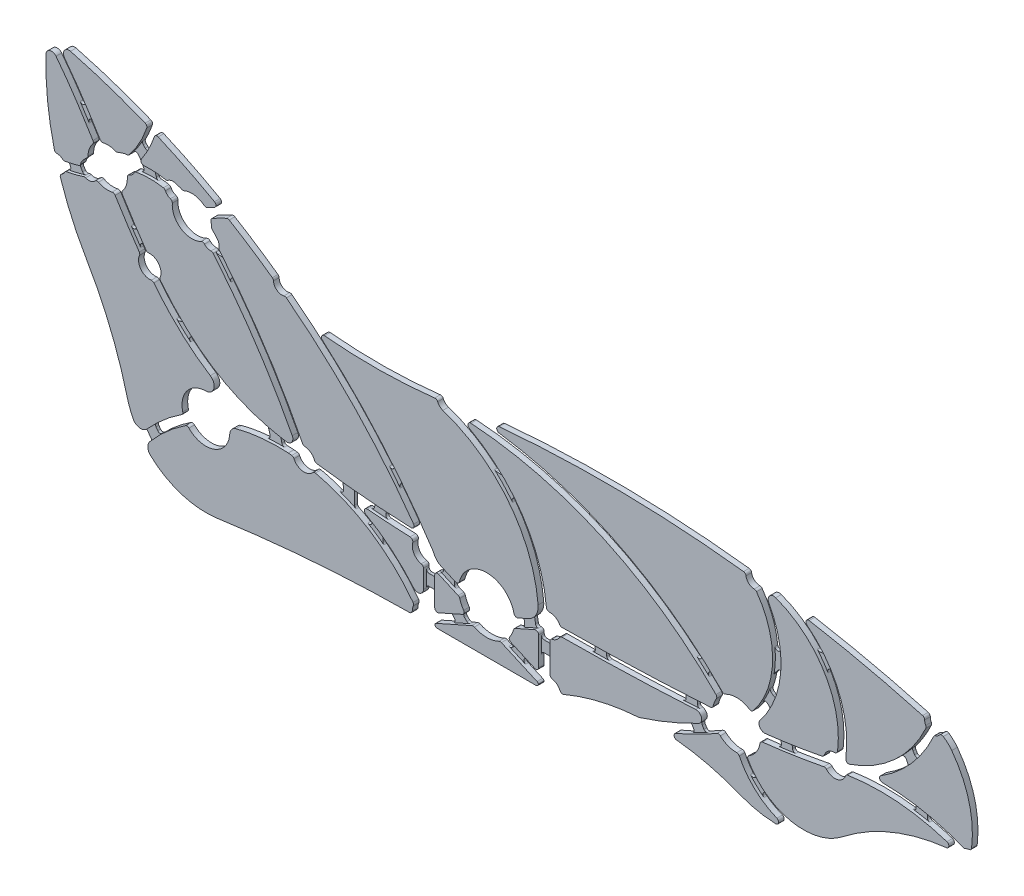
SolidWorks part; units mm, degrees
material "ｴﾎﾟｷｼ樹脂(充填剤なし)"
ref_plane "正面" through (0, 0, 0) normal (0, 0, 1) x (1, 0, 0)
ref_plane "平面" through (0, 0, 0) normal (0, 1, 0) x (1, 0, 0)
ref_plane "右側面" through (0, 0, 0) normal (1, 0, 0) x (0, 0, -1)
sketch "ｽｹｯﾁ1" plane through (0, 0, 0) normal (0, 0, 1) x (1, 0, 0)
  line L1 (22.5, 0.101) -> (22.5, -10.101)
  line L2 (22.5, 0.101) -> (22.5, -10.101)
  line L3 (-22.5, -6.4126) -> (-22.5, 0.101)
  line L4 (-22.5, -6.4126) -> (-22.5, 0.101)
  line L6 (11.119, 1.5832) -> (14.7807, 3.2107)
  line L7 (-17.0939, -10.9558) -> (-8.626, -7.1923)
  line L8 (-18.5, 0.042) -> (-18.5, -10.042)
  line L9 (-10.1663, -2.1231) -> (-17.0939, 0.9558)
  line L10 (-17.0939, -10.9558) -> (-8.626, -7.1923)
  line L11 (-18.5, 0.042) -> (-18.5, -10.042)
  line L12 (-10.1663, -2.1231) -> (-17.0939, 0.9558)
  line L13 (8.626, -7.1923) -> (17.0939, -10.9558)
  line L14 (17.0939, 0.9558) -> (10.1663, -2.1231)
  line L15 (18.5, -10.042) -> (18.5, 0.042)
  line L16 (8.626, -7.1923) -> (17.0939, -10.9558)
  line L17 (17.0939, 0.9558) -> (10.1663, -2.1231)
  line L18 (18.5, -10.042) -> (18.5, 0.042)
  line L19 (-16.2024, 3.8425) -> (-11.119, 1.5832)
  line L20 (11.119, 1.5832) -> (14.7807, 3.2107)
  line L21 (-16.2024, 3.8425) -> (-11.119, 1.5832)
  line L23 (-17.5, -16) -> (17.5, -16)
  line L24 (-5.2366, -8.9688) -> (-17.9339, -14.6121)
  line L25 (17.9339, -14.6121) -> (5.2366, -8.9688)
  line L26 (-17.5, -16) -> (17.5, -16)
  line L27 (-5.2366, -8.9688) -> (-17.9339, -14.6121)
  line L28 (17.9339, -14.6121) -> (5.2366, -8.9688)
  arc A26 (83.2113, 1.2758) -> (89.0603, -0.9998) centre (89, 7.5) ccw
  arc A27 (89.967, -1.5631) -> (89.0603, -0.9998) centre (89.0674, -1.9998) ccw
  arc A28 (89.967, -1.5631) -> (103.3566, -14.0607) centre (112.8701, 9.5532) ccw
  arc A29 (102.9573, -15.9879) -> (103.3566, -14.0607) centre (102.9829, -14.9883) ccw
  arc A30 (90.1176, -13.3365) -> (102.9573, -15.9879) centre (103.9017, 21) ccw
  arc A31 (90.1176, -13.3365) -> (67.6378, -7.8134) centre (59.3978, -89.8605) ccw
  arc A32 (67.3468, -5.898) -> (67.6378, -7.8134) centre (67.7378, -6.8184) ccw
  arc A33 (67.3468, -5.898) -> (82.0317, 1.4104) centre (13.9413, 119.818) ccw
  arc A34 (83.2113, 1.2758) -> (82.0317, 1.4104) centre (82.5302, 0.5435) ccw
  arc A35 (83.2113, 1.2758) -> (89.0603, -0.9998) centre (89, 7.5) ccw
  arc A36 (89.967, -1.5631) -> (89.0603, -0.9998) centre (89.0674, -1.9998) ccw
  arc A37 (89.967, -1.5631) -> (103.3566, -14.0607) centre (112.8701, 9.5532) ccw
  arc A38 (102.9573, -15.9879) -> (103.3566, -14.0607) centre (102.9829, -14.9883) ccw
  arc A39 (90.1176, -13.3365) -> (102.9573, -15.9879) centre (103.9017, 21) ccw
  arc A40 (90.1176, -13.3365) -> (67.6378, -7.8134) centre (59.3978, -89.8605) ccw
  arc A41 (67.3468, -5.898) -> (67.6378, -7.8134) centre (67.7378, -6.8184) ccw
  arc A42 (67.3468, -5.898) -> (82.0317, 1.4104) centre (13.9413, 119.818) ccw
  arc A43 (83.2113, 1.2758) -> (82.0317, 1.4104) centre (82.5302, 0.5435) ccw
  arc A45 (129.2172, 15.4989) -> (156.4002, 40.1644) centre (114.0417, 59.5347) ccw
  arc A46 (127.9008, 16.5808) -> (129.2172, 15.4989) centre (128.8914, 16.4443) ccw
  arc A47 (127.9008, 16.5808) -> (114.0595, 50.8962) centre (91.0356, 21.6602) ccw
  arc A48 (163.9203, 8.9775) -> (128.5572, 11.8079) centre (140.2604, -64.3004) ccw
  arc A49 (163.7257, 7.0322) -> (163.9203, 8.9775) centre (163.613, 8.0259) ccw
  arc A50 (163.7257, 7.0322) -> (126.7209, -8.1253) centre (172, -65.9175) ccw
  arc A51 (93.0844, -1.0722) -> (126.7209, -8.1253) centre (112.8701, 9.5532) ccw
  arc A52 (93.4427, 0.2535) -> (93.0844, -1.0722) centre (93.9654, -0.5991) ccw
  arc A53 (93.4427, 0.2535) -> (97.3718, 6.0294) centre (89, 7.5) ccw
  arc A54 (98.2474, 6.8503) -> (97.3718, 6.0294) centre (98.3567, 5.8563) ccw
  arc A55 (98.2474, 6.8503) -> (120.0633, 10.1693) centre (69.0994, 271.8045) ccw
  arc A56 (121.0036, 9.8502) -> (120.0633, 10.1693) centre (120.2545, 9.1877) ccw
  arc A57 (121.0036, 9.8502) -> (127.7673, 11.1556) centre (124, 12.5) ccw
  arc A58 (128.5572, 11.8079) -> (127.7673, 11.1556) centre (128.7091, 10.8195) ccw
  arc A59 (163.9203, 8.9775) -> (128.5572, 11.8079) centre (140.2604, -64.3004) ccw
  arc A60 (163.7257, 7.0322) -> (163.9203, 8.9775) centre (163.613, 8.0259) ccw
  arc A61 (163.7257, 7.0322) -> (126.7209, -8.1253) centre (172, -65.9175) ccw
  arc A62 (93.0844, -1.0722) -> (126.7209, -8.1253) centre (112.8701, 9.5532) ccw
  arc A63 (93.4427, 0.2535) -> (93.0844, -1.0722) centre (93.9654, -0.5991) ccw
  arc A64 (93.4427, 0.2535) -> (97.3718, 6.0294) centre (89, 7.5) ccw
  arc A65 (98.2474, 6.8503) -> (97.3718, 6.0294) centre (98.3567, 5.8563) ccw
  arc A66 (98.2474, 6.8503) -> (120.0633, 10.1693) centre (69.0994, 271.8045) ccw
  arc A67 (121.0036, 9.8502) -> (120.0633, 10.1693) centre (120.2545, 9.1877) ccw
  arc A68 (121.0036, 9.8502) -> (127.7673, 11.1556) centre (124, 12.5) ccw
  arc A69 (128.5572, 11.8079) -> (127.7673, 11.1556) centre (128.7091, 10.8195) ccw
  arc A70 (114.85, 52.6669) -> (114.0595, 50.8962) centre (114.6782, 51.6818) ccw
  arc A71 (155.2686, 43.5545) -> (114.85, 52.6669) centre (42.29, -363.3692) ccw
  arc A72 (156.0008, 42.5682) -> (155.2686, 43.5545) centre (155.001, 42.5909) ccw
  arc A73 (156.0008, 42.5682) -> (156.3681, 41.0602) centre (159, 42.5) ccw
  arc A74 (156.4002, 40.1644) -> (156.3681, 41.0602) centre (155.4908, 40.5803) ccw
  arc A75 (129.2172, 15.4989) -> (156.4002, 40.1644) centre (114.0417, 59.5347) ccw
  arc A76 (127.9008, 16.5808) -> (129.2172, 15.4989) centre (128.8914, 16.4443) ccw
  arc A77 (127.9008, 16.5808) -> (114.0595, 50.8962) centre (91.0356, 21.6602) ccw
  arc A78 (114.85, 52.6669) -> (114.0595, 50.8962) centre (114.6782, 51.6818) ccw
  arc A79 (155.2686, 43.5545) -> (114.85, 52.6669) centre (42.29, -363.3692) ccw
  arc A80 (156.0008, 42.5682) -> (155.2686, 43.5545) centre (155.001, 42.5909) ccw
  arc A81 (156.0008, 42.5682) -> (156.3681, 41.0602) centre (159, 42.5) ccw
  arc A82 (156.4002, 40.1644) -> (156.3681, 41.0602) centre (155.4908, 40.5803) ccw
  arc A83 (97.4246, 13.2154) -> (99.214, 9.978) centre (98.9855, 11.9649) ccw
  arc A84 (97.4246, 13.2154) -> (100.5051, 50.879) centre (71.0713, 34.3286) ccw
  arc A85 (93.5868, 14.6562) -> (85.0963, 15.0506) centre (89, 7.5) ccw
  arc A86 (171.786, 10.4924) -> (170.5639, 10.1339) centre (172, 7.5) ccw
  arc A87 (169.717, 10.0822) -> (170.5639, 10.1339) centre (170.0852, 11.0119) ccw
  arc A88 (169.717, 10.0822) -> (140.9263, 15.6997) centre (140.2604, -64.3004) ccw
  arc A89 (140.4029, 17.5466) -> (140.9263, 15.6997) centre (140.9346, 16.6997) ccw
  arc A90 (140.4029, 17.5466) -> (159.198, 39.0695) centre (114.0417, 59.5347) ccw
  arc A91 (159.8316, 39.6176) -> (159.198, 39.0695) centre (160.1088, 38.6568) ccw
  arc A92 (159.8316, 39.6176) -> (161.317, 40.5944) centre (159, 42.5) ccw
  arc A93 (162.6526, 40.7855) -> (161.317, 40.5944) centre (162.0894, 39.9592) ccw
  arc A94 (165.6353, 37.9447) -> (162.6526, 40.7855) centre (155.4945, 30.2837) ccw
  arc A95 (172.7066, 11.3632) -> (165.6353, 37.9447) centre (136.5587, 15.9784) ccw
  arc A96 (171.786, 10.4924) -> (172.7066, 11.3632) centre (171.7146, 11.4898) ccw
  arc A97 (171.786, 10.4924) -> (170.5639, 10.1339) centre (172, 7.5) ccw
  arc A98 (169.717, 10.0822) -> (170.5639, 10.1339) centre (170.0852, 11.0119) ccw
  arc A99 (169.717, 10.0822) -> (140.9263, 15.6997) centre (140.2604, -64.3004) ccw
  arc A100 (140.4029, 17.5466) -> (140.9263, 15.6997) centre (140.9346, 16.6997) ccw
  arc A101 (140.4029, 17.5466) -> (159.198, 39.0695) centre (114.0417, 59.5347) ccw
  arc A102 (159.8316, 39.6176) -> (159.198, 39.0695) centre (160.1088, 38.6568) ccw
  arc A103 (159.8316, 39.6176) -> (161.317, 40.5944) centre (159, 42.5) ccw
  arc A104 (162.6526, 40.7855) -> (161.317, 40.5944) centre (162.0894, 39.9592) ccw
  arc A105 (165.6353, 37.9447) -> (162.6526, 40.7855) centre (155.4945, 30.2837) ccw
  arc A106 (172.7066, 11.3632) -> (165.6353, 37.9447) centre (136.5587, 15.9784) ccw
  arc A107 (171.786, 10.4924) -> (172.7066, 11.3632) centre (171.7146, 11.4898) ccw
  arc A108 (83.9236, 15.238) -> (85.0963, 15.0506) centre (84.637, 15.9389) ccw
  arc A109 (83.9236, 15.238) -> (4.4224, 55.2639) centre (-14.6672, -81.6202) ccw
  arc A110 (4.471, 57.2503) -> (4.4224, 55.2639) centre (4.5606, 56.2543) ccw
  arc A111 (91.4838, 56.0721) -> (4.471, 57.2503) centre (42.29, -363.3692) ccw
  arc A112 (92.3587, 55.2099) -> (91.4838, 56.0721) centre (91.3673, 55.0789) ccw
  arc A113 (92.3587, 55.2099) -> (95.319, 52.6028) centre (95.3328, 55.6027) ccw
  arc A114 (96.1287, 52.1831) -> (95.319, 52.6028) centre (95.3143, 51.6028) ccw
  arc A115 (94.9009, 14.8656) -> (96.1287, 52.1831) centre (71.0713, 34.3286) ccw
  arc A116 (93.5868, 14.6562) -> (94.9009, 14.8656) centre (94.1264, 15.4981) ccw
  arc A117 (93.5868, 14.6562) -> (85.0963, 15.0506) centre (89, 7.5) ccw
  arc A118 (83.9236, 15.238) -> (85.0963, 15.0506) centre (84.637, 15.9389) ccw
  arc A119 (83.9236, 15.238) -> (4.4224, 55.2639) centre (-14.6672, -81.6202) ccw
  arc A120 (4.471, 57.2503) -> (4.4224, 55.2639) centre (4.5606, 56.2543) ccw
  arc A121 (91.4838, 56.0721) -> (4.471, 57.2503) centre (42.29, -363.3692) ccw
  arc A122 (92.3587, 55.2099) -> (91.4838, 56.0721) centre (91.3673, 55.0789) ccw
  arc A123 (92.3587, 55.2099) -> (95.319, 52.6028) centre (95.3328, 55.6027) ccw
  arc A124 (96.1287, 52.1831) -> (95.319, 52.6028) centre (95.3143, 51.6028) ccw
  arc A125 (94.9009, 14.8656) -> (96.1287, 52.1831) centre (71.0713, 34.3286) ccw
  arc A126 (93.5868, 14.6562) -> (94.9009, 14.8656) centre (94.1264, 15.4981) ccw
  arc A127 (81.6673, 13.2539) -> (-5.6096, 53.2849) centre (-14.6672, -81.6202) ccw
  arc A128 (81.8017, 12.0204) -> (81.6673, 13.2539) centre (80.9548, 12.5522) ccw
  arc A129 (81.8017, 12.0204) -> (80.6633, 9.158) centre (89, 7.5) ccw
  arc A130 (79.7472, 8.3552) -> (80.6633, 9.158) centre (79.6825, 9.3531) ccw
  arc A131 (26.8289, 6.5106) -> (79.7472, 8.3552) centre (22.5, 890.7) ccw
  arc A132 (25.9592, 7.0085) -> (26.8289, 6.5106) centre (26.824, 7.5106) ccw
  arc A133 (25.9592, 7.0085) -> (22.314, 8.9957) centre (22.5, 5) ccw
  arc A134 (21.2718, 9.9017) -> (22.314, 8.9957) centre (22.2675, 9.9946) ccw
  arc A135 (21.2718, 9.9017) -> (-6.1525, 51.4076) centre (-31.2679, 5) ccw
  arc A136 (-5.6096, 53.2849) -> (-6.1525, 51.4076) centre (-5.6766, 52.2871) ccw
  arc A137 (81.6673, 13.2539) -> (-5.6096, 53.2849) centre (-14.6672, -81.6202) ccw
  arc A138 (81.8017, 12.0204) -> (81.6673, 13.2539) centre (80.9548, 12.5522) ccw
  arc A139 (81.8017, 12.0204) -> (80.6633, 9.158) centre (89, 7.5) ccw
  arc A140 (79.7472, 8.3552) -> (80.6633, 9.158) centre (79.6825, 9.3531) ccw
  arc A141 (26.8289, 6.5106) -> (79.7472, 8.3552) centre (22.5, 890.7) ccw
  arc A142 (25.9592, 7.0085) -> (26.8289, 6.5106) centre (26.824, 7.5106) ccw
  arc A143 (25.9592, 7.0085) -> (22.314, 8.9957) centre (22.5, 5) ccw
  arc A144 (21.2718, 9.9017) -> (22.314, 8.9957) centre (22.2675, 9.9946) ccw
  arc A145 (21.2718, 9.9017) -> (-6.1525, 51.4076) centre (-31.2679, 5) ccw
  arc A146 (-5.6096, 53.2849) -> (-6.1525, 51.4076) centre (-5.6766, 52.2871) ccw
  arc A147 (102.9446, 53.7342) -> (100.5051, 50.879) centre (102.2484, 51.8592) ccw
  arc A148 (23.3, 1.0808) -> (25.969, 3.0085) centre (22.5, 5) ccw
  arc A149 (26.8313, 3.5106) -> (25.969, 3.0085) centre (26.8362, 2.5106) ccw
  arc A150 (26.8313, 3.5106) -> (74.4485, 5.0222) centre (22.5, 890.7) ccw
  arc A151 (75.487, 1.2505) -> (74.4485, 5.0222) centre (74.5656, 3.0256) ccw
  arc A152 (54.3014, -7.5287) -> (75.487, 1.2505) centre (13.9413, 119.818) ccw
  arc A153 (54.0639, -7.5734) -> (54.3014, -7.5287) centre (53.9993, -6.5755) ccw
  arc A154 (54.0639, -7.5734) -> (27.4366, -13.8466) centre (59.3978, -89.8605) ccw
  arc A155 (26.1392, -13.3399) -> (27.4366, -13.8466) centre (27.049, -12.9248) ccw
  arc A156 (26.1392, -13.3399) -> (23.3, -11.0808) centre (22.5, -15) ccw
  arc A157 (22.5, -10.101) -> (23.3, -11.0808) centre (23.5, -10.101) ccw
  arc A158 (23.3, 1.0808) -> (22.5, 0.101) centre (23.5, 0.101) ccw
  arc A159 (23.3, 1.0808) -> (25.969, 3.0085) centre (22.5, 5) ccw
  arc A160 (26.8313, 3.5106) -> (25.969, 3.0085) centre (26.8362, 2.5106) ccw
  arc A161 (26.8313, 3.5106) -> (74.4485, 5.0222) centre (22.5, 890.7) ccw
  arc A162 (75.487, 1.2505) -> (74.4485, 5.0222) centre (74.5656, 3.0256) ccw
  arc A163 (54.3014, -7.5287) -> (75.487, 1.2505) centre (13.9413, 119.818) ccw
  arc A164 (54.0639, -7.5734) -> (54.3014, -7.5287) centre (53.9993, -6.5755) ccw
  arc A165 (54.0639, -7.5734) -> (27.4366, -13.8466) centre (59.3978, -89.8605) ccw
  arc A166 (26.1392, -13.3399) -> (27.4366, -13.8466) centre (27.049, -12.9248) ccw
  arc A167 (26.1392, -13.3399) -> (23.3, -11.0808) centre (22.5, -15) ccw
  arc A168 (22.5, -10.101) -> (23.3, -11.0808) centre (23.5, -10.101) ccw
  arc A169 (23.3, 1.0808) -> (22.5, 0.101) centre (23.5, 0.101) ccw
  arc A170 (124.9796, 17.3747) -> (102.9446, 53.7342) centre (91.0356, 21.6602) ccw
  arc A171 (123.99, 16.5) -> (124.9796, 17.3747) centre (123.9875, 17.5) ccw
  arc A172 (123.99, 16.5) -> (120.207, 13.7702) centre (124, 12.5) ccw
  arc A179 (119.4498, 13.1062) -> (120.207, 13.7702) centre (119.2588, 14.0878) ccw
  arc A180 (99.214, 9.978) -> (119.4498, 13.1062) centre (69.0994, 271.8045) ccw
  arc A181 (97.4246, 13.2154) -> (99.214, 9.978) centre (98.9855, 11.9649) ccw
  arc A182 (97.4246, 13.2154) -> (100.5051, 50.879) centre (71.0713, 34.3286) ccw
  arc A183 (102.9446, 53.7342) -> (100.5051, 50.879) centre (102.2484, 51.8592) ccw
  arc A184 (124.9796, 17.3747) -> (102.9446, 53.7342) centre (91.0356, 21.6602) ccw
  arc A185 (123.99, 16.5) -> (124.9796, 17.3747) centre (123.9875, 17.5) ccw
  arc A186 (123.99, 16.5) -> (120.207, 13.7702) centre (124, 12.5) ccw
  arc A187 (119.4498, 13.1062) -> (120.207, 13.7702) centre (119.2588, 14.0878) ccw
  arc A188 (99.214, 9.978) -> (119.4498, 13.1062) centre (69.0994, 271.8045) ccw
  arc A196 (-9.6113, -2.7608) -> (-8.2111, -5.7077) centre (0, 0) ccw
  arc A197 (-8.626, -7.1923) -> (-8.2111, -5.7077) centre (-9.0322, -6.2785) ccw
  arc A198 (-26.3403, 6.1191) -> (-23.3, 1.0808) centre (-22.5, 5) ccw
  arc A199 (-22.5, 0.101) -> (-23.3, 1.0808) centre (-23.5, 0.101) ccw
  arc A200 (-26.0294, -7.7013) -> (-22.5, -6.4126) centre (-24.5, -6.4126) ccw
  arc A201 (-150.204, 61.7869) -> (-145.3266, 62.9598) centre (-156.5, 98.6967) ccw
  arc A202 (-151.0229, 62.0134) -> (-150.204, 61.7869) centre (-150.3722, 62.7727) ccw
  arc A203 (-151.0229, 62.0134) -> (-152.9962, 62.7355) centre (-152.9752, 59.7355) ccw
  arc A204 (-153.9743, 63.4967) -> (-152.9962, 62.7355) centre (-153.0032, 63.7354) ccw
  arc A205 (-156.9587, 91.4184) -> (-153.9743, 63.4967) centre (-52.35, 88.479) ccw
  arc A206 (-153.3843, 92.5946) -> (-156.9587, 91.4184) centre (-154.9595, 91.3622) ccw
  arc A207 (-140.3274, 72.022) -> (-140.2368, 73.1947) centre (-141.0885, 72.6707) ccw
  arc A208 (-92.6465, 72.9722) -> (-97.7506, 70.3671) centre (-65, 12.5) ccw
  arc A209 (-91.7165, 72.9204) -> (-92.6465, 72.9722) centre (-92.2307, 72.0627) ccw
  arc A210 (-76.3493, 62.7985) -> (-91.7165, 72.9204) centre (-203.2901, -113.1988) ccw
  arc A211 (-75.9352, 62.0305) -> (-76.3493, 62.7985) centre (-76.9343, 61.9874) ccw
  arc A212 (-75.9352, 62.0305) -> (-72.1979, 59.2524) centre (-72.938, 62.1596) ccw
  arc A213 (-71.3431, 59.0772) -> (-72.1979, 59.2524) centre (-71.9512, 58.2833) ccw
  arc A214 (-26.022, 11.9612) -> (-71.3431, 59.0772) centre (-203.2901, -113.1988) ccw
  arc A215 (-26.8783, 10.3852) -> (-26.022, 11.9612) centre (-26.8389, 11.3844) ccw
  arc A216 (-60.4936, 13.364) -> (-26.8783, 10.3852) centre (-13.2682, 355.1295) ccw
  arc A217 (-61.2853, 13.9837) -> (-60.4936, 13.364) centre (-60.3567, 14.3546) ccw
  arc A218 (-61.2853, 13.9837) -> (-64.7539, 16.4924) centre (-65, 12.5) ccw
  arc A219 (-65.5834, 17.0366) -> (-64.7539, 16.4924) centre (-64.6924, 17.4905) ccw
  arc A220 (-65.5834, 17.0366) -> (-95.1344, 61.7139) centre (-276.8279, -90.5756) ccw
  arc A221 (-95.3497, 62.5466) -> (-95.1344, 61.7139) centre (-94.368, 62.3562) ccw
  arc A222 (-95.3497, 62.5466) -> (-96.0213, 65.0748) centre (-98.2949, 63.1176) ccw
  arc A223 (-96.0213, 65.0748) -> (-97.7054, 66.8832) centre (-120, 44.4324) ccw
  arc A224 (-98.0007, 67.5789) -> (-97.7054, 66.8832) centre (-97.0008, 67.5928) ccw
  arc A225 (-98.0007, 67.5789) -> (-98.2258, 69.2449) centre (-105, 67.4812) ccw
  arc A226 (-97.7506, 70.3671) -> (-98.2258, 69.2449) centre (-97.2581, 69.4969) ccw
  arc A227 (-92.6465, 72.9722) -> (-97.7506, 70.3671) centre (-65, 12.5) ccw
  arc A228 (-91.7165, 72.9204) -> (-92.6465, 72.9722) centre (-92.2307, 72.0627) ccw
  arc A229 (-76.3493, 62.7985) -> (-91.7165, 72.9204) centre (-203.2901, -113.1988) ccw
  arc A230 (-75.9352, 62.0305) -> (-76.3493, 62.7985) centre (-76.9343, 61.9874) ccw
  arc A231 (-75.9352, 62.0305) -> (-72.1979, 59.2524) centre (-72.938, 62.1596) ccw
  arc A232 (-71.3431, 59.0772) -> (-72.1979, 59.2524) centre (-71.9512, 58.2833) ccw
  arc A233 (-26.022, 11.9612) -> (-71.3431, 59.0772) centre (-203.2901, -113.1988) ccw
  arc A234 (-26.8783, 10.3852) -> (-26.022, 11.9612) centre (-26.8389, 11.3844) ccw
  arc A235 (-60.4936, 13.364) -> (-26.8783, 10.3852) centre (-13.2682, 355.1295) ccw
  arc A236 (-61.2853, 13.9837) -> (-60.4936, 13.364) centre (-60.3567, 14.3546) ccw
  arc A237 (-61.2853, 13.9837) -> (-64.7539, 16.4924) centre (-65, 12.5) ccw
  arc A238 (-65.5834, 17.0366) -> (-64.7539, 16.4924) centre (-64.6924, 17.4905) ccw
  arc A239 (-65.5834, 17.0366) -> (-95.1344, 61.7139) centre (-276.8279, -90.5756) ccw
  arc A240 (-95.3497, 62.5466) -> (-95.1344, 61.7139) centre (-94.368, 62.3562) ccw
  arc A241 (-95.3497, 62.5466) -> (-96.0213, 65.0748) centre (-98.2949, 63.1176) ccw
  arc A242 (-96.0213, 65.0748) -> (-97.7054, 66.8832) centre (-120, 44.4324) ccw
  arc A243 (-98.0007, 67.5789) -> (-97.7054, 66.8832) centre (-97.0008, 67.5928) ccw
  arc A244 (-98.0007, 67.5789) -> (-98.2258, 69.2449) centre (-105, 67.4812) ccw
  arc A245 (-97.7506, 70.3671) -> (-98.2258, 69.2449) centre (-97.2581, 69.4969) ccw
  arc A246 (-140.3274, 72.022) -> (-141.9993, 67.5789) centre (-135, 67.4812) ccw
  arc A247 (-142.2946, 66.8832) -> (-141.9993, 67.5789) centre (-142.9992, 67.5928) ccw
  arc A248 (-142.2946, 66.8832) -> (-143.9787, 65.0748) centre (-120, 44.4324) ccw
  arc A249 (-143.9787, 65.0748) -> (-144.645, 63.7151) centre (-141.7051, 63.1176) ccw
  arc A250 (-145.3266, 62.9598) -> (-144.645, 63.7151) centre (-145.625, 63.9142) ccw
  arc A251 (-150.204, 61.7869) -> (-145.3266, 62.9598) centre (-156.5, 98.6967) ccw
  arc A252 (-151.0229, 62.0134) -> (-150.204, 61.7869) centre (-150.3722, 62.7727) ccw
  arc A253 (-151.0229, 62.0134) -> (-152.9962, 62.7355) centre (-152.9752, 59.7355) ccw
  arc A254 (-153.9743, 63.4967) -> (-152.9962, 62.7355) centre (-153.0032, 63.7354) ccw
  arc A255 (-156.9587, 91.4184) -> (-153.9743, 63.4967) centre (-52.35, 88.479) ccw
  arc A256 (-153.3843, 92.5946) -> (-156.9587, 91.4184) centre (-154.9595, 91.3622) ccw
  arc A257 (-140.3274, 72.022) -> (-140.2368, 73.1947) centre (-141.0885, 72.6707) ccw
  arc A258 (-140.3274, 72.022) -> (-141.9993, 67.5789) centre (-135, 67.4812) ccw
  arc A259 (-142.2946, 66.8832) -> (-141.9993, 67.5789) centre (-142.9992, 67.5928) ccw
  arc A260 (-142.2946, 66.8832) -> (-143.9787, 65.0748) centre (-120, 44.4324) ccw
  arc A261 (-143.9787, 65.0748) -> (-144.645, 63.7151) centre (-141.7051, 63.1176) ccw
  arc A262 (-145.3266, 62.9598) -> (-144.645, 63.7151) centre (-145.625, 63.9142) ccw
  arc A263 (-26.0294, -7.7013) -> (-43.0938, 6.4818) centre (-74.1755, -48.2713) ccw
  arc A264 (-42.5161, 8.3479) -> (-43.0938, 6.4818) centre (-42.6001, 7.3514) ccw
  arc A265 (-42.5161, 8.3479) -> (-27.2601, 7.398) centre (-13.2682, 355.1295) ccw
  arc A266 (-122.9876, 76.0572) -> (-118.3344, 85.3171) centre (-156.5, 98.6967) ccw
  arc A267 (-116.993, 85.9037) -> (-118.3344, 85.3171) centre (-117.3907, 84.9862) ccw
  arc A268 (-96.9469, 75.9576) -> (-116.993, 85.9037) centre (-203.2901, -113.1988) ccw
  arc A269 (-96.9768, 74.198) -> (-96.9469, 75.9576) centre (-97.4369, 75.0859) ccw
  arc A270 (-96.9768, 74.198) -> (-99.4771, 72.8365) centre (-65, 12.5) ccw
  arc A271 (-100.6016, 72.9268) -> (-99.4771, 72.8365) centre (-99.9733, 73.7047) ccw
  arc A272 (-100.6016, 72.9268) -> (-107.7452, 73.9205) centre (-105, 67.4812) ccw
  arc A273 (-108.5008, 73.9088) -> (-107.7452, 73.9205) centre (-108.1373, 74.8404) ccw
  arc A274 (-108.5008, 73.9088) -> (-110.8362, 74.7163) centre (-120, 44.4324) ccw
  arc A275 (-110.8362, 74.7163) -> (-113.5331, 74.2236) centre (-111.7051, 71.8449) ccw
  arc A276 (-114.3306, 74.0344) -> (-113.5331, 74.2236) centre (-114.1425, 75.0165) ccw
  arc A277 (-114.3306, 74.0344) -> (-122.0896, 74.4999) centre (-120, 44.4324) ccw
  arc A278 (-122.9876, 76.0572) -> (-122.0896, 74.4999) centre (-122.1589, 75.4974) ccw
  arc A279 (-122.9876, 76.0572) -> (-118.3344, 85.3171) centre (-156.5, 98.6967) ccw
  arc A280 (-116.993, 85.9037) -> (-118.3344, 85.3171) centre (-117.3907, 84.9862) ccw
  arc A281 (-96.9469, 75.9576) -> (-116.993, 85.9037) centre (-203.2901, -113.1988) ccw
  arc A282 (-96.9768, 74.198) -> (-96.9469, 75.9576) centre (-97.4369, 75.0859) ccw
  arc A283 (-96.9768, 74.198) -> (-99.4771, 72.8365) centre (-65, 12.5) ccw
  arc A284 (-100.6016, 72.9268) -> (-99.4771, 72.8365) centre (-99.9733, 73.7047) ccw
  arc A285 (-100.6016, 72.9268) -> (-107.7452, 73.9205) centre (-105, 67.4812) ccw
  arc A286 (-108.5008, 73.9088) -> (-107.7452, 73.9205) centre (-108.1373, 74.8404) ccw
  arc A287 (-108.5008, 73.9088) -> (-110.8362, 74.7163) centre (-120, 44.4324) ccw
  arc A288 (-110.8362, 74.7163) -> (-113.5331, 74.2236) centre (-111.7051, 71.8449) ccw
  arc A289 (-114.3306, 74.0344) -> (-113.5331, 74.2236) centre (-114.1425, 75.0165) ccw
  arc A290 (-114.3306, 74.0344) -> (-122.0896, 74.4999) centre (-120, 44.4324) ccw
  arc A291 (-122.9876, 76.0572) -> (-122.0896, 74.4999) centre (-122.1589, 75.4974) ccw
  arc A292 (-26.3403, 6.1191) -> (-27.2601, 7.398) centre (-27.3003, 6.3988) ccw
  arc A293 (-26.3403, 6.1191) -> (-23.3, 1.0808) centre (-22.5, 5) ccw
  arc A294 (-22.5, 0.101) -> (-23.3, 1.0808) centre (-23.5, 0.101) ccw
  arc A295 (-26.0294, -7.7013) -> (-22.5, -6.4126) centre (-24.5, -6.4126) ccw
  arc A296 (-106.0705, 1.5503) -> (-91.5134, 7.0221) centre (-100, 7.5) ccw
  arc A297 (-89.2736, 9.7568) -> (-91.5134, 7.0221) centre (-88.5182, 6.8535) ccw
  arc A298 (-70.6824, 11.5869) -> (-89.2736, 9.7568) centre (-74.1755, -48.2713) ccw
  arc A299 (-70.604, 11.5793) -> (-70.6824, 11.5869) centre (-70.7407, 10.5886) ccw
  arc A300 (-70.604, 11.5793) -> (-69.4305, 11.426) centre (-59.3082, 93.4746) ccw
  arc A301 (-68.6424, 10.8468) -> (-69.4305, 11.426) centre (-69.553, 10.4335) ccw
  arc A302 (-68.6424, 10.8468) -> (-61.9641, 9.8955) centre (-65, 12.5) ccw
  arc A303 (-60.9851, 10.2199) -> (-61.9641, 9.8955) centre (-61.2051, 9.2444) ccw
  arc A304 (-26.225, -12.2719) -> (-60.9851, 10.2199) centre (-74.1755, -48.2713) ccw
  arc A305 (-26.1198, -13.2978) -> (-26.225, -12.2719) centre (-27.0247, -12.8723) ccw
  arc A306 (-26.1198, -13.2978) -> (-26.5, -15.0192) centre (-22.5, -15) ccw
  arc A307 (-27.4903, -16.024) -> (-26.5, -15.0192) centre (-27.4999, -15.024) ccw
  arc A308 (-27.4903, -16.024) -> (-95.9045, -21.2094) centre (-22.5, -535.7727) ccw
  arc A309 (-119.7512, -13.7341) -> (-95.9045, -21.2094) centre (-100, 7.5) ccw
  arc A310 (-120.0008, -9.6028) -> (-119.7512, -13.7341) centre (-117.708, -11.5375) ccw
  arc A311 (-107.3377, 1.6835) -> (-120.0008, -9.6028) centre (-74.1755, -48.2713) ccw
  arc A312 (-106.0705, 1.5503) -> (-107.3377, 1.6835) centre (-106.7847, 0.8503) ccw
  arc A313 (-106.0705, 1.5503) -> (-91.5134, 7.0221) centre (-100, 7.5) ccw
  arc A314 (-89.2736, 9.7568) -> (-91.5134, 7.0221) centre (-88.5182, 6.8535) ccw
  arc A315 (-70.6824, 11.5869) -> (-89.2736, 9.7568) centre (-74.1755, -48.2713) ccw
  arc A316 (-70.604, 11.5793) -> (-70.6824, 11.5869) centre (-70.7407, 10.5886) ccw
  arc A317 (-70.604, 11.5793) -> (-69.4305, 11.426) centre (-59.3082, 93.4746) ccw
  arc A318 (-68.6424, 10.8468) -> (-69.4305, 11.426) centre (-69.553, 10.4335) ccw
  arc A319 (-68.6424, 10.8468) -> (-61.9641, 9.8955) centre (-65, 12.5) ccw
  arc A320 (-60.9851, 10.2199) -> (-61.9641, 9.8955) centre (-61.2051, 9.2444) ccw
  arc A321 (-26.225, -12.2719) -> (-60.9851, 10.2199) centre (-74.1755, -48.2713) ccw
  arc A322 (-26.1198, -13.2978) -> (-26.225, -12.2719) centre (-27.0247, -12.8723) ccw
  arc A323 (-26.1198, -13.2978) -> (-26.5, -15.0192) centre (-22.5, -15) ccw
  arc A324 (-27.4903, -16.024) -> (-26.5, -15.0192) centre (-27.4999, -15.024) ccw
  arc A325 (-27.4903, -16.024) -> (-95.9045, -21.2094) centre (-22.5, -535.7727) ccw
  arc A326 (-119.7512, -13.7341) -> (-95.9045, -21.2094) centre (-100, 7.5) ccw
  arc A327 (-120.0008, -9.6028) -> (-119.7512, -13.7341) centre (-117.708, -11.5375) ccw
  arc A328 (-107.3377, 1.6835) -> (-120.0008, -9.6028) centre (-74.1755, -48.2713) ccw
  arc A329 (-106.0705, 1.5503) -> (-107.3377, 1.6835) centre (-106.7847, 0.8503) ccw
  arc A330 (-26.0294, -7.7013) -> (-43.0938, 6.4818) centre (-74.1755, -48.2713) ccw
  arc A331 (-42.5161, 8.3479) -> (-43.0938, 6.4818) centre (-42.6001, 7.3514) ccw
  arc A332 (-42.5161, 8.3479) -> (-27.2601, 7.398) centre (-13.2682, 355.1295) ccw
  arc A333 (-26.3403, 6.1191) -> (-27.2601, 7.398) centre (-27.3003, 6.3988) ccw
  arc A334 (-18.5, -10.042) -> (-17.0939, -10.9558) centre (-17.5, -10.042) ccw
  arc A335 (-17.0939, 0.9558) -> (-18.5, 0.042) centre (-17.5, 0.042) ccw
  arc A336 (-9.6113, -2.7608) -> (-10.1663, -2.1231) centre (-10.5725, -3.0369) ccw
  arc A337 (-148.2331, 96.7006) -> (-150.3263, 93.5472) centre (-148.7406, 94.766) ccw
  arc A338 (-121.6343, 87.8518) -> (-148.2331, 96.7006) centre (-203.2901, -113.1988) ccw
  arc A339 (-121.0642, 86.6023) -> (-121.6343, 87.8518) centre (-122.0106, 86.9253) ccw
  arc A340 (-127.3364, 75.2137) -> (-121.0642, 86.6023) centre (-156.5, 98.6967) ccw
  arc A341 (-128.1602, 74.8418) -> (-127.3364, 75.2137) centre (-128.1152, 75.8408) ccw
  arc A342 (-128.1602, 74.8418) -> (-129.1638, 74.7163) centre (-128.2949, 71.8449) ccw
  arc A343 (-129.1638, 74.7163) -> (-131.4992, 73.9088) centre (-120, 44.4324) ccw
  arc A344 (-132.2548, 73.9205) -> (-131.4992, 73.9088) centre (-131.8627, 74.8404) ccw
  arc A345 (-100.5079, 61.0921) -> (-98.2079, 60.1189) centre (-98.2949, 63.1176) ccw
  arc A346 (-97.4124, 59.7615) -> (-98.2079, 60.1189) centre (-98.1789, 59.1193) ccw
  arc A347 (-69.2577, 17.6177) -> (-97.4124, 59.7615) centre (-276.8279, -90.5756) ccw
  arc A348 (-71.3333, 14.7162) -> (-69.2577, 17.6177) centre (-71.0313, 16.6932) ccw
  arc A349 (-116.299, 42.915) -> (-116.1539, 41.9101) centre (-115.3737, 42.5356) ccw
  arc A350 (-116.299, 42.915) -> (-120.4118, 48.4111) centre (-120, 44.4324) ccw
  arc A351 (-121.3328, 48.8307) -> (-120.4118, 48.4111) centre (-120.5147, 49.4058) ccw
  arc A352 (-129.6706, 62.9428) -> (-129.7605, 61.7697) centre (-128.9093, 62.2944) ccw
  arc A353 (-129.6706, 62.9428) -> (-128.0179, 67.9818) centre (-135, 67.4812) ccw
  arc A354 (-127.3391, 69.0012) -> (-128.0179, 67.9818) centre (-127.0205, 68.0533) ccw
  arc A355 (-127.3391, 69.0012) -> (-125.5769, 70.575) centre (-128.2949, 71.8449) ccw
  arc A356 (-124.8496, 71.1356) -> (-125.5769, 70.575) centre (-124.6709, 70.1517) ccw
  arc A357 (-115.1504, 71.1356) -> (-124.8496, 71.1356) centre (-120, 44.4324) ccw
  arc A358 (-114.4231, 70.575) -> (-115.1504, 71.1356) centre (-115.3291, 70.1517) ccw
  arc A359 (-114.4231, 70.575) -> (-112.6609, 69.0012) centre (-111.7051, 71.8449) ccw
  arc A360 (-111.9821, 67.9818) -> (-112.6609, 69.0012) centre (-112.9795, 68.0533) ccw
  arc A361 (-111.9821, 67.9818) -> (-101.7149, 61.3) centre (-105, 67.4812) ccw
  arc A362 (-100.5079, 61.0921) -> (-101.7149, 61.3) centre (-101.2456, 60.4169) ccw
  arc A363 (-100.5079, 61.0921) -> (-98.2079, 60.1189) centre (-98.2949, 63.1176) ccw
  arc A364 (-97.4124, 59.7615) -> (-98.2079, 60.1189) centre (-98.1789, 59.1193) ccw
  arc A365 (-69.2577, 17.6177) -> (-97.4124, 59.7615) centre (-276.8279, -90.5756) ccw
  arc A366 (-71.3333, 14.7162) -> (-69.2577, 17.6177) centre (-71.0313, 16.6932) ccw
  arc A367 (-116.299, 42.915) -> (-116.1539, 41.9101) centre (-115.3737, 42.5356) ccw
  arc A368 (-116.299, 42.915) -> (-120.4118, 48.4111) centre (-120, 44.4324) ccw
  arc A369 (-121.3328, 48.8307) -> (-120.4118, 48.4111) centre (-120.5147, 49.4058) ccw
  arc A370 (-129.6706, 62.9428) -> (-129.7605, 61.7697) centre (-128.9093, 62.2944) ccw
  arc A371 (-129.6706, 62.9428) -> (-128.0179, 67.9818) centre (-135, 67.4812) ccw
  arc A372 (-127.3391, 69.0012) -> (-128.0179, 67.9818) centre (-127.0205, 68.0533) ccw
  arc A373 (-127.3391, 69.0012) -> (-125.5769, 70.575) centre (-128.2949, 71.8449) ccw
  arc A374 (-124.8496, 71.1356) -> (-125.5769, 70.575) centre (-124.6709, 70.1517) ccw
  arc A375 (-115.1504, 71.1356) -> (-124.8496, 71.1356) centre (-120, 44.4324) ccw
  arc A376 (-114.4231, 70.575) -> (-115.1504, 71.1356) centre (-115.3291, 70.1517) ccw
  arc A377 (-114.4231, 70.575) -> (-112.6609, 69.0012) centre (-111.7051, 71.8449) ccw
  arc A378 (-111.9821, 67.9818) -> (-112.6609, 69.0012) centre (-112.9795, 68.0533) ccw
  arc A379 (-111.9821, 67.9818) -> (-101.7149, 61.3) centre (-105, 67.4812) ccw
  arc A380 (-100.5079, 61.0921) -> (-101.7149, 61.3) centre (-101.2456, 60.4169) ccw
  arc A381 (-132.2548, 73.9205) -> (-136.5911, 74.298) centre (-135, 67.4812) ccw
  arc A382 (-137.6701, 74.7478) -> (-136.5911, 74.298) centre (-136.8184, 75.2718) ccw
  arc A383 (-148.2331, 96.7006) -> (-150.3263, 93.5472) centre (-148.7406, 94.766) ccw
  arc A384 (-121.6343, 87.8518) -> (-148.2331, 96.7006) centre (-203.2901, -113.1988) ccw
  arc A385 (-121.0642, 86.6023) -> (-121.6343, 87.8518) centre (-122.0106, 86.9253) ccw
  arc A386 (-127.3364, 75.2137) -> (-121.0642, 86.6023) centre (-156.5, 98.6967) ccw
  arc A387 (-128.1602, 74.8418) -> (-127.3364, 75.2137) centre (-128.1152, 75.8408) ccw
  arc A388 (-128.1602, 74.8418) -> (-129.1638, 74.7163) centre (-128.2949, 71.8449) ccw
  arc A389 (-129.1638, 74.7163) -> (-131.4992, 73.9088) centre (-120, 44.4324) ccw
  arc A390 (-132.2548, 73.9205) -> (-131.4992, 73.9088) centre (-131.8627, 74.8404) ccw
  arc A391 (-132.2548, 73.9205) -> (-136.5911, 74.298) centre (-135, 67.4812) ccw
  arc A392 (-137.6701, 74.7478) -> (-136.5911, 74.298) centre (-136.8184, 75.2718) ccw
  arc A393 (-9.6113, -2.7608) -> (-8.2111, -5.7077) centre (0, 0) ccw
  arc A394 (-8.626, -7.1923) -> (-8.2111, -5.7077) centre (-9.0322, -6.2785) ccw
  arc A396 (-18.5, -10.042) -> (-17.0939, -10.9558) centre (-17.5, -10.042) ccw
  arc A397 (-17.0939, 0.9558) -> (-18.5, 0.042) centre (-17.5, 0.042) ccw
  arc A398 (-9.6113, -2.7608) -> (-10.1663, -2.1231) centre (-10.5725, -3.0369) ccw
  arc A399 (8.2111, -5.7077) -> (8.626, -7.1923) centre (9.0322, -6.2785) ccw
  arc A400 (8.2111, -5.7077) -> (9.6113, -2.7608) centre (0, 0) ccw
  arc A401 (10.1663, -2.1231) -> (9.6113, -2.7608) centre (10.5725, -3.0369) ccw
  arc A402 (18.5, 0.042) -> (17.0939, 0.9558) centre (17.5, 0.042) ccw
  arc A403 (17.0939, -10.9558) -> (18.5, -10.042) centre (17.5, -10.042) ccw
  arc A404 (8.2111, -5.7077) -> (8.626, -7.1923) centre (9.0322, -6.2785) ccw
  arc A405 (8.2111, -5.7077) -> (9.6113, -2.7608) centre (0, 0) ccw
  arc A406 (10.1663, -2.1231) -> (9.6113, -2.7608) centre (10.5725, -3.0369) ccw
  arc A407 (18.5, 0.042) -> (17.0939, 0.9558) centre (17.5, 0.042) ccw
  arc A408 (17.0939, -10.9558) -> (18.5, -10.042) centre (17.5, -10.042) ccw
  arc A411 (-18.4772, -15.2121) -> (-17.5, -16) centre (-17.5, -15) ccw
  arc A412 (-17.9339, -14.6121) -> (-18.4772, -15.2121) centre (-17.5277, -15.5259) ccw
  arc A413 (-4.3913, -8.9842) -> (-5.2366, -8.9688) centre (-4.8304, -9.8827) ccw
  arc A414 (-4.3913, -8.9842) -> (4.3913, -8.9842) centre (0, 0) ccw
  arc A415 (5.2366, -8.9688) -> (4.3913, -8.9842) centre (4.8304, -9.8827) ccw
  arc A416 (-19.152, 7.1889) -> (-58.4992, 52.4382) centre (-203.2901, -113.1988) ccw
  arc A417 (-57.7478, 54.1867) -> (-58.4992, 52.4382) centre (-57.841, 53.1911) ccw
  arc A418 (-57.7478, 54.1867) -> (-18.4998, 54.6068) centre (-40.1338, 242.1889) ccw
  arc A419 (-17.4557, 53.9822) -> (-18.4998, 54.6068) centre (-18.3852, 53.6134) ccw
  arc A420 (-17.4557, 53.9822) -> (-15.611, 52.2409) centre (-14.6672, 55.0886) ccw
  arc A421 (18.3225, 9.1999) -> (-15.611, 52.2409) centre (-31.2679, 5) ccw
  arc A422 (14.7807, 3.2107) -> (18.3225, 9.1999) centre (12.3439, 8.6935) ccw
  arc A423 (9.7389, 2.27) -> (11.119, 1.5832) centre (10.7128, 2.4971) ccw
  arc A424 (9.7389, 2.27) -> (-9.7389, 2.27) centre (0, 0) ccw
  arc A425 (-11.119, 1.5832) -> (-9.7389, 2.27) centre (-10.7128, 2.4971) ccw
  arc A426 (-18.7985, 6.5163) -> (-16.2024, 3.8425) centre (-14.1717, 8.4116) ccw
  arc A427 (-18.7985, 6.5163) -> (-19.152, 7.1889) centre (-22.5, 5) ccw
  arc A428 (-19.152, 7.1889) -> (-58.4992, 52.4382) centre (-203.2901, -113.1988) ccw
  arc A429 (-57.7478, 54.1867) -> (-58.4992, 52.4382) centre (-57.841, 53.1911) ccw
  arc A430 (-57.7478, 54.1867) -> (-18.4998, 54.6068) centre (-40.1338, 242.1889) ccw
  arc A431 (-17.4557, 53.9822) -> (-18.4998, 54.6068) centre (-18.3852, 53.6134) ccw
  arc A432 (-17.4557, 53.9822) -> (-15.611, 52.2409) centre (-14.6672, 55.0886) ccw
  arc A433 (18.3225, 9.1999) -> (-15.611, 52.2409) centre (-31.2679, 5) ccw
  arc A434 (14.7807, 3.2107) -> (18.3225, 9.1999) centre (12.3439, 8.6935) ccw
  arc A435 (9.7389, 2.27) -> (11.119, 1.5832) centre (10.7128, 2.4971) ccw
  arc A436 (9.7389, 2.27) -> (-9.7389, 2.27) centre (0, 0) ccw
  arc A437 (-11.119, 1.5832) -> (-9.7389, 2.27) centre (-10.7128, 2.4971) ccw
  arc A438 (-18.7985, 6.5163) -> (-16.2024, 3.8425) centre (-14.1717, 8.4116) ccw
  arc A439 (-18.7985, 6.5163) -> (-19.152, 7.1889) centre (-22.5, 5) ccw
  arc A440 (18.4772, -15.2121) -> (17.9339, -14.6121) centre (17.5277, -15.5259) ccw
  arc A441 (17.5, -16) -> (18.4772, -15.2121) centre (17.5, -15) ccw
  arc A442 (-18.4772, -15.2121) -> (-17.5, -16) centre (-17.5, -15) ccw
  arc A443 (-17.9339, -14.6121) -> (-18.4772, -15.2121) centre (-17.5277, -15.5259) ccw
  arc A444 (-4.3913, -8.9842) -> (-5.2366, -8.9688) centre (-4.8304, -9.8827) ccw
  arc A445 (-4.3913, -8.9842) -> (4.3913, -8.9842) centre (0, 0) ccw
  arc A446 (5.2366, -8.9688) -> (4.3913, -8.9842) centre (4.8304, -9.8827) ccw
  arc A447 (18.4772, -15.2121) -> (17.9339, -14.6121) centre (17.5277, -15.5259) ccw
  arc A448 (17.5, -16) -> (18.4772, -15.2121) centre (17.5, -15) ccw
  arc A462 (-151.8369, 56.0141) -> (-142.5363, 35.3937) centre (-52.35, 88.479) ccw
  arc A463 (-151.4085, 57.1771) -> (-151.8369, 56.0141) centre (-150.8863, 56.3243) ccw
  arc A464 (-151.4085, 57.1771) -> (-150.3258, 58.3282) centre (-152.9752, 59.7355) ccw
  arc A465 (-149.6129, 58.8445) -> (-150.3258, 58.3282) centre (-149.4426, 57.8591) ccw
  arc A466 (-149.6129, 58.8445) -> (-143.571, 60.3761) centre (-156.5, 98.6967) ccw
  arc A467 (-142.8648, 60.3508) -> (-143.571, 60.3761) centre (-143.2514, 59.4285) ccw
  arc A468 (-142.8648, 60.3508) -> (-139.4921, 61.0921) centre (-141.7051, 63.1176) ccw
  arc A469 (-138.2851, 61.3) -> (-139.4921, 61.0921) centre (-138.7544, 60.4169) ccw
  arc A470 (-138.2851, 61.3) -> (-133.4061, 60.6651) centre (-135, 67.4812) ccw
  arc A471 (-132.3271, 60.2161) -> (-133.4061, 60.6651) centre (-133.1784, 59.6914) ccw
  arc A472 (-123.6518, 46.0647) -> (-123.7469, 47.0482) centre (-124.5647, 46.4728) ccw
  arc A473 (-123.6518, 46.0647) -> (-119.4644, 40.4684) centre (-120, 44.4324) ccw
  arc A474 (-118.5498, 40.1024) -> (-119.4644, 40.4684) centre (-119.3305, 39.4774) ccw
  arc A475 (-100.0397, 15.9999) -> (-98.4481, 21.534) centre (-100.0538, 18.9999) ccw
  arc A476 (-100.0397, 15.9999) -> (-108.2539, 5.4693) centre (-100, 7.5) ccw
  arc A477 (-108.6769, 4.3939) -> (-108.2539, 5.4693) centre (-109.2249, 5.2304) ccw
  arc A478 (-108.6769, 4.3939) -> (-120.9994, -6.1821) centre (-74.1755, -48.2713) ccw
  arc A479 (-125.9109, -5.5239) -> (-120.9994, -6.1821) centre (-123.2305, -4.1766) ccw
  arc A480 (-128.1038, 0.346) -> (-125.9109, -5.5239) centre (-100, 7.5) ccw
  arc A481 (-128.1038, 0.346) -> (-142.5363, 35.3937) centre (-258.447, -32.8336) ccw
  arc A482 (-151.8369, 56.0141) -> (-142.5363, 35.3937) centre (-52.35, 88.479) ccw
  arc A483 (-151.4085, 57.1771) -> (-151.8369, 56.0141) centre (-150.8863, 56.3243) ccw
  arc A484 (-151.4085, 57.1771) -> (-150.3258, 58.3282) centre (-152.9752, 59.7355) ccw
  arc A485 (-149.6129, 58.8445) -> (-150.3258, 58.3282) centre (-149.4426, 57.8591) ccw
  arc A486 (-149.6129, 58.8445) -> (-143.571, 60.3761) centre (-156.5, 98.6967) ccw
  arc A487 (-142.8648, 60.3508) -> (-143.571, 60.3761) centre (-143.2514, 59.4285) ccw
  arc A488 (-142.8648, 60.3508) -> (-139.4921, 61.0921) centre (-141.7051, 63.1176) ccw
  arc A489 (-138.2851, 61.3) -> (-139.4921, 61.0921) centre (-138.7544, 60.4169) ccw
  arc A490 (-138.2851, 61.3) -> (-133.4061, 60.6651) centre (-135, 67.4812) ccw
  arc A491 (-132.3271, 60.2161) -> (-133.4061, 60.6651) centre (-133.1784, 59.6914) ccw
  arc A492 (-123.6518, 46.0647) -> (-123.7469, 47.0482) centre (-124.5647, 46.4728) ccw
  arc A493 (-123.6518, 46.0647) -> (-119.4644, 40.4684) centre (-120, 44.4324) ccw
  arc A494 (-118.5498, 40.1024) -> (-119.4644, 40.4684) centre (-119.3305, 39.4774) ccw
  arc A495 (-100.0397, 15.9999) -> (-98.4481, 21.534) centre (-100.0538, 18.9999) ccw
  arc A496 (-100.0397, 15.9999) -> (-108.2539, 5.4693) centre (-100, 7.5) ccw
  arc A497 (-108.6769, 4.3939) -> (-108.2539, 5.4693) centre (-109.2249, 5.2304) ccw
  arc A498 (-108.6769, 4.3939) -> (-120.9994, -6.1821) centre (-74.1755, -48.2713) ccw
  arc A499 (-125.9109, -5.5239) -> (-120.9994, -6.1821) centre (-123.2305, -4.1766) ccw
  arc A500 (-128.1038, 0.346) -> (-125.9109, -5.5239) centre (-100, 7.5) ccw
  arc A501 (-128.1038, 0.346) -> (-142.5363, 35.3937) centre (-258.447, -32.8336) ccw
  spline S1 degree 3 poles (1517.8313, 1168.1726) (-95.1119, -225.0148) (-75.0035, -16.2871) (-208.7618, 169.9004) (-343.4627, 159.6431) (-2149.1942, 204.309) knots -2.836055 -2.836055 -2.836055 -2.836055 0.161129 0.224621 2.556451 2.556451 2.556451 2.556451 only from (-140.2368, 73.1947) to (-153.3843, 92.5946)
  spline S2 degree 3 poles (-140.2368, 73.1947) (-142.6963, 77.1924) (-146.6577, 83.4533) (-151.1896, 89.7616) (-153.1045, 92.2369) (-153.3843, 92.5946) knots 0.052704 0.052704 0.052704 0.052704 0.161129 0.224621 0.23541 0.23541 0.23541 0.23541
  spline S3 degree 3 poles (-1914.6085, -831.331) (-351.8359, 204.7339) (-47.2103, 151.7391) (-101.1138, -214.595) (1427.0499, 1302.833) knots -2.481302 -2.481302 -2.481302 -2.481302 0.122909 3.100951 3.100951 3.100951 3.100951 only from (-150.3263, 93.5472) to (-137.6701, 74.7478)
  spline S4 degree 3 poles (-1779.0948, -1037.8988) (-96.6396, 446.8526) (-203.1747, 123.4352) (-104.7873, 29.8043) (-98.7908, 25.1729) (-92.1812, 21.2004) (-86.0823, 18.5061) (-80.7979, 16.7625) (-76.6208, 15.6719) (6.6462, -0.6213) (206.4443, 107.82) (1855.2656, 551.4195) knots -2.57603 -2.57603 -2.57603 -2.57603 0.614547 0.676001 0.737456 0.798911 0.860365 0.891093 0.92182 0.952547 2.631746 2.631746 2.631746 2.631746 only from (-116.1539, 41.9101) to (-71.3333, 14.7162)
  spline S5 degree 3 poles (-1788.2568, -1031.5008) (-226.0088, 324.2801) (-164.7255, 15.0029) (28.533, -94.3464) (1453.2213, 1268.3596) knots -2.529256 -2.529256 -2.529256 -2.529256 0.368728 3.130199 3.130199 3.130199 3.130199 only from (-129.7605, 61.7697) to (-121.3328, 48.8307)
  spline S6 degree 3 poles (-116.1539, 41.9101) (-114.2523, 39.5383) (-110.6059, 35.3415) (-104.7873, 29.8043) (-98.7908, 25.1729) (-92.1812, 21.2004) (-86.0823, 18.5061) (-80.7979, 16.7625) (-76.6208, 15.6719) (-73.4094, 15.0435) (-71.6145, 14.7591) (-71.3333, 14.7162) knots 0.541498 0.541498 0.541498 0.541498 0.614547 0.676001 0.737456 0.798911 0.860365 0.891093 0.92182 0.952547 0.958224 0.958224 0.958224 0.958224
  spline S7 degree 3 poles (-129.7605, 61.7697) (-129.3888, 61.1667) (-126.6544, 56.7509) (-123.8603, 52.4258) (-121.3328, 48.8307) knots 0.352317 0.352317 0.352317 0.352317 0.368728 0.472764 0.472764 0.472764 0.472764
  spline S8 degree 3 poles (-150.3263, 93.5472) (-148.7089, 91.4428) (-144.3002, 85.3367) (-140.2405, 78.9257) (-137.6701, 74.7478) knots 0.061431 0.061431 0.061431 0.061431 0.122909 0.235584 0.235584 0.235584 0.235584
  spline S10 degree 3 poles (1511.7956, 1181.8537) (38.9406, -102.9452) (-182.0605, 22.1541) (-213.8854, 315.4507) (-1747.8535, -1098.3505) knots -2.268431 -2.268431 -2.268431 -2.268431 0.444483 3.351436 3.351436 3.351436 3.351436 only from (-123.7469, 47.0482) to (-132.3271, 60.2161)
  spline S11 degree 3 poles (1436.4894, 1292.742) (210.898, 52.5019) (-30.2952, -40.3407) (-207.7383, 117.4496) (-78.1945, 432.5976) (-1740.8063, -1105.3528) knots -1.797383 -1.797383 -1.797383 -1.797383 0.597595 0.661087 3.774372 3.774372 3.774372 3.774372 only from (-98.4481, 21.534) to (-118.5498, 40.1024)
  spline S12 degree 3 poles (-123.7469, 47.0482) (-126.0322, 50.2959) (-128.8953, 54.6843) (-131.6705, 59.1509) (-132.3271, 60.2161) knots 0.352132 0.352132 0.352132 0.352132 0.444483 0.473304 0.473304 0.473304 0.473304
  spline S13 degree 3 poles (-98.4481, 21.534) (-100.5388, 22.8587) (-104.7593, 25.8761) (-111.5871, 31.9477) (-116.0386, 36.9654) (-118.5498, 40.1024) knots 0.540807 0.540807 0.540807 0.540807 0.597595 0.661087 0.755203 0.755203 0.755203 0.755203
  dimension "D3" = 0
  dimension "D5" = 0
  dimension "D6" = 0
  dimension "D7" = 0
  dimension "D8" = 0
  dimension "D9" = 0
  dimension "D10" = 0
  dimension "D11" = 0
  dimension "D16" = 0
  dimension "D17" = 0
  dimension "D19" = 0
  dimension "D20" = 0
  dimension "D21" = 0
  dimension "D22" = 0
  dimension "D23" = 0
  dimension "D24" = 0
  dimension "D25" = 0
  dimension "D26" = 0
  dimension "D27" = 0
  dimension "D28" = 0
extrude "ﾎﾞｽ - 押し出し1" add sketch "ｽｹｯﾁ1" against normal blind 2
sketch "ｽｹｯﾁ2" plane through (0, 0, -2) normal (0, 0, -1) x (-1, 0, 0)
  line L0 (18.5, -0.5) -> (18.5, -6.5) construction
  line L1 (19.5, -5.5) -> (21.5013, -5.5) construction
  line L2 (22.5, -6.4126) -> (22.5, -0.5) construction
  line L3 (21.5, -1.5) -> (19.5, -1.5) construction
  line L4 (11.8977, -1.3536) -> (17.0939, 0.9558) construction
  line L5 (16.2024, 3.8425) -> (11.119, 1.5832) construction
  line L6 (6.968, -9.7384) -> (12.8413, -12.3487) construction
  line L7 (14.3069, -9.7172) -> (8.626, -7.1923) construction
  line L8 (-8.626, -7.1923) -> (-14.3069, -9.7172) construction
  line L9 (-12.8413, -12.3487) -> (-6.968, -9.7384) construction
  line L10 (-11.119, 1.5832) -> (-14.7807, 3.2107) construction
  line L11 (-17.0939, 0.9558) -> (-11.8977, -1.3536) construction
  line L12 (-18.5, -6.5) -> (-18.5, -0.5) construction
  line L13 (-19.5, -1.5) -> (-21.5, -1.5) construction
  line L14 (-22.5, -0.5) -> (-22.5, -6.5) construction
  line L15 (-21.5, -5.5) -> (-19.5, -5.5) construction
  line L16 (18.5, -0.5) -> (18.5, -6.5)
  line L17 (19.5, -5.5) -> (21.5013, -5.5)
  line L18 (22.5, -6.4126) -> (22.5, -0.5)
  line L19 (21.5, -1.5) -> (19.5, -1.5)
  line L20 (11.8977, -1.3536) -> (17.0939, 0.9558)
  line L21 (16.2024, 3.8425) -> (11.119, 1.5832)
  line L22 (6.968, -9.7384) -> (12.8413, -12.3487)
  line L23 (14.3069, -9.7172) -> (8.626, -7.1923)
  line L24 (-8.626, -7.1923) -> (-14.3069, -9.7172)
  line L25 (-12.8413, -12.3487) -> (-6.968, -9.7384)
  line L26 (-11.119, 1.5832) -> (-14.7807, 3.2107)
  line L27 (-17.0939, 0.9558) -> (-11.8977, -1.3536)
  line L28 (-18.5, -6.5) -> (-18.5, -0.5)
  line L29 (-19.5, -1.5) -> (-21.5, -1.5)
  line L30 (-22.5, -0.5) -> (-22.5, -6.5)
  line L31 (-21.5, -5.5) -> (-19.5, -5.5)
  arc A0 (97.4036, 59.751) -> (92.0018, 53.0575) centre (276.8279, -90.5756) ccw construction
  arc A1 (96.7005, 59.3952) -> (97.4036, 59.751) centre (96.6371, 60.3932) ccw construction
  arc A2 (96.7005, 59.3952) -> (95.3353, 59.2903) centre (100, 7.5) ccw construction
  arc A3 (94.4764, 60.9254) -> (95.3353, 59.2903) centre (95.2456, 60.2863) ccw construction
  arc A4 (94.4764, 60.9254) -> (88.9142, 53.9687) centre (276.8279, -90.5756) ccw construction
  arc A5 (89.4879, 54.3348) -> (88.9142, 53.9687) centre (89.7069, 53.359) ccw construction
  arc A6 (91.0252, 54.6535) -> (89.4879, 54.3348) centre (100, 7.5) ccw construction
  arc A7 (92.0018, 53.0575) -> (91.0252, 54.6535) centre (91.2122, 53.6711) ccw construction
  arc A8 (123.4954, 81.0143) -> (126.7445, 75.9683) centre (156.5, 98.6967) ccw construction
  arc A9 (123.302, 79.8165) -> (123.4954, 81.0143) centre (122.6139, 80.5421) ccw construction
  arc A10 (123.302, 79.8165) -> (122.6064, 79.1173) centre (135, 67.4812) ccw construction
  arc A11 (120.9996, 79.3228) -> (122.6064, 79.1173) centre (121.8774, 79.8018) ccw construction
  arc A12 (120.9996, 79.3228) -> (122.9876, 76.0572) centre (156.5, 98.6967) ccw construction
  arc A13 (122.0896, 74.4999) -> (122.9876, 76.0572) centre (122.1589, 75.4974) ccw construction
  arc A14 (122.0896, 74.4999) -> (117.971, 74.504) centre (120, 44.4324) ccw construction
  arc A15 (118.9806, 73.1715) -> (117.971, 74.504) centre (118.0383, 73.5063) ccw construction
  arc A16 (118.9806, 73.1715) -> (118.6684, 72.2012) centre (135, 67.4812) ccw construction
  arc A17 (117.7892, 71.4822) -> (118.6684, 72.2012) centre (117.7077, 72.4789) ccw construction
  arc A18 (123.8616, 71.2962) -> (117.7892, 71.4822) centre (120, 44.4324) ccw construction
  arc A19 (123.0876, 72.6865) -> (123.8616, 71.2962) centre (124.0039, 72.2861) ccw construction
  arc A20 (125.1957, 76.0179) -> (123.0876, 72.6865) centre (135, 67.4812) ccw construction
  arc A21 (126.7445, 75.9683) -> (125.1957, 76.0179) centre (125.9498, 75.3612) ccw construction
  arc A22 (144.3919, 81.6513) -> (145.779, 81.9341) centre (144.9444, 82.4849) ccw construction
  arc A23 (144.3919, 81.6513) -> (143.5905, 82.1511) centre (135, 67.4812) ccw construction
  arc A24 (143.261, 83.5647) -> (143.5905, 82.1511) centre (144.0958, 83.014) ccw construction
  arc A25 (141.3325, 78.8346) -> (139.999, 78.4939) centre (140.8453, 77.9613) ccw construction
  arc A26 (142.2556, 78.2681) -> (141.3325, 78.8346) centre (135, 67.4812) ccw construction
  arc A27 (142.5439, 76.9057) -> (142.2556, 78.2681) centre (141.6975, 77.4383) ccw construction
  arc A28 (145.3266, 62.9598) -> (150.204, 61.7869) centre (156.5, 98.6967) ccw construction
  arc A29 (145.1305, 63.045) -> (145.3266, 62.9598) centre (145.625, 63.9142) ccw construction
  arc A30 (145.512, 61.6936) -> (145.1305, 63.045) centre (144.636, 62.1759) ccw construction
  arc A31 (144.8983, 60.6971) -> (145.512, 61.6936) centre (135, 67.4812) ccw construction
  arc A32 (143.7584, 60.3134) -> (144.8983, 60.6971) centre (144.0734, 61.2624) ccw construction
  arc A33 (143.7584, 60.3134) -> (149.6129, 58.8445) centre (156.5, 98.6967) ccw construction
  arc A34 (149.7879, 58.7976) -> (149.6129, 58.8445) centre (149.4426, 57.8591) ccw construction
  arc A35 (149.243, 60.1917) -> (149.7879, 58.7976) centre (150.1332, 59.7361) ccw construction
  arc A36 (149.243, 60.1917) -> (149.7081, 61.1827) centre (135, 67.4812) ccw construction
  arc A37 (150.4998, 61.7808) -> (149.7081, 61.1827) centre (150.6274, 60.789) ccw construction
  arc A38 (150.204, 61.7869) -> (150.4998, 61.7808) centre (150.3722, 62.7727) ccw construction
  arc A39 (126.2382, 52.3949) -> (127.5799, 52.7112) centre (126.7428, 53.2583) ccw construction
  arc A40 (126.2382, 52.3949) -> (125.3849, 52.8829) centre (100, 7.5) ccw construction
  arc A41 (125.0362, 54.303) -> (125.3849, 52.8829) centre (125.8731, 53.7556) ccw construction
  arc A42 (122.984, 49.6395) -> (121.6851, 49.3337) centre (122.5052, 48.7615) ccw construction
  arc A43 (123.8798, 49.1384) -> (122.984, 49.6395) centre (100, 7.5) ccw construction
  arc A44 (124.2028, 47.6992) -> (123.8798, 49.1384) centre (123.3823, 48.2709) ccw construction
  arc A45 (118.1403, -5.8109) -> (118.7487, -4.9394) centre (100, 7.5) ccw construction
  arc A46 (116.6261, -5.9255) -> (118.1403, -5.8109) centre (117.334, -5.2193) ccw construction
  arc A47 (120.0008, -9.6028) -> (116.6261, -5.9255) centre (74.1755, -48.2713) ccw construction
  arc A48 (120.4284, -10.2727) -> (120.0008, -9.6028) centre (117.708, -11.5375) ccw construction
  arc A49 (120.5593, -9.2202) -> (120.4284, -10.2727) centre (121.3352, -9.8511) ccw construction
  arc A50 (120.5593, -9.2202) -> (121.8032, -7.5623) centre (100, 7.5) ccw construction
  arc A51 (122.7771, -7.1422) -> (121.8032, -7.5623) centre (122.6259, -8.1307) ccw construction
  arc A52 (120.9994, -6.1821) -> (122.7771, -7.1422) centre (123.2305, -4.1766) ccw construction
  arc A53 (120.9994, -6.1821) -> (118.6213, -3.6782) centre (74.1755, -48.2713) ccw construction
  arc A54 (118.7487, -4.9394) -> (118.6213, -3.6782) centre (117.9154, -4.3865) ccw construction
  arc A55 (110.3611, 31.8905) -> (111.4623, 32.107) centre (110.752, 32.8109) ccw construction
  arc A56 (110.3611, 31.8905) -> (109.3896, 32.2807) centre (100, 7.5) ccw construction
  arc A57 (109.0372, 33.9233) -> (109.3896, 32.2807) centre (109.7439, 33.2159) ccw construction
  arc A58 (104.8104, 29.4798) -> (103.9558, 29.2705) centre (104.5967, 28.5029) ccw construction
  arc A59 (106.0636, 29.1676) -> (104.8104, 29.4798) centre (100, 7.5) ccw construction
  arc A60 (106.4425, 27.4432) -> (106.0636, 29.1676) centre (105.7941, 28.2046) ccw construction
  arc A61 (74.2566, 13.7872) -> (73.1109, 15.0091) centre (73.2852, 14.0244) ccw construction
  arc A62 (74.2566, 13.7872) -> (73.9739, 12.489) centre (100, 7.5) ccw construction
  arc A63 (73.0112, 11.6775) -> (73.9739, 12.489) centre (72.9917, 12.6773) ccw construction
  arc A64 (79.0067, 11.4938) -> (73.0112, 11.6775) centre (74.1755, -48.2713) ccw construction
  arc A65 (78.1145, 12.7227) -> (79.0067, 11.4938) centre (79.0872, 12.4906) ccw construction
  arc A66 (79.1406, 15.9343) -> (78.1145, 12.7227) centre (100, 7.5) ccw construction
  arc A67 (79.7994, 16.5228) -> (79.1406, 15.9343) centre (80.0677, 15.5594) ccw construction
  arc A68 (47.0035, 11.7699) -> (53.0488, 12.4177) centre (13.2682, 355.1295) ccw construction
  arc A69 (48.0994, 10.7129) -> (47.0035, 11.7699) centre (47.1013, 10.7747) ccw construction
  arc A70 (48.0994, 10.7129) -> (48.0133, 6.3256) centre (100, 7.5) ccw construction
  arc A71 (47.4591, 5.4078) -> (48.0133, 6.3256) centre (47.0135, 6.303) ccw construction
  arc A72 (53.3679, 7.9626) -> (47.4591, 5.4078) centre (74.1755, -48.2713) ccw construction
  arc A73 (52.0213, 8.9303) -> (53.3679, 7.9626) centre (53.0209, 8.9005) ccw construction
  arc A74 (52.1676, 11.5079) -> (52.0213, 8.9303) centre (100, 7.5) ccw construction
  arc A75 (53.0488, 12.4177) -> (52.1676, 11.5079) centre (53.1641, 11.4244) ccw construction
  arc A76 (-116.7749, 44.2002) -> (-120.6012, 38.8775) centre (-91.0356, 21.6602) ccw construction
  arc A77 (-117.7234, 43.8784) -> (-116.7749, 44.2002) centre (-117.5272, 44.859) ccw construction
  arc A78 (-117.7234, 43.8784) -> (-118.8299, 44.0796) centre (-124, 12.5) ccw construction
  arc A79 (-119.4313, 45.7128) -> (-118.8299, 44.0796) centre (-118.6683, 45.0664) ccw construction
  arc A80 (-119.4313, 45.7128) -> (-123.4422, 39.9538) centre (-91.0356, 21.6602) ccw construction
  arc A81 (-122.5185, 40.4608) -> (-123.4422, 39.9538) centre (-122.5714, 39.4622) ccw construction
  arc A82 (-121.3715, 40.3764) -> (-122.5185, 40.4608) centre (-124, 12.5) ccw construction
  arc A83 (-120.6012, 38.8775) -> (-121.3715, 40.3764) centre (-121.4654, 39.3808) ccw construction
  arc A84 (-4.7812, 43.5345) -> (-11.4064, 36.038) centre (31.2679, 5) ccw construction
  arc A85 (-10.8841, 36.4079) -> (-11.4064, 36.038) centre (-10.5976, 35.4498) ccw construction
  arc A86 (-9.2711, 36.8517) -> (-10.8841, 36.4079) centre (0, 0) ccw construction
  arc A87 (-8.2334, 35.2736) -> (-9.2711, 36.8517) centre (-9.0271, 35.8819) ccw construction
  arc A88 (-1.8136, 42.1814) -> (-8.2334, 35.2736) centre (31.2679, 5) ccw construction
  arc A89 (-2.4207, 41.9302) -> (-1.8136, 42.1814) centre (-2.4783, 42.9285) ccw construction
  arc A90 (-2.4207, 41.9302) -> (-4.0028, 41.8088) centre (0, 0) ccw construction
  arc A91 (-4.7812, 43.5345) -> (-4.0028, 41.8088) centre (-4.0981, 42.8043) ccw construction
  arc A92 (35.6215, 24.5556) -> (31.7306, 19.6784) centre (203.2901, -113.1988) ccw construction
  arc A93 (34.0384, 24.6046) -> (35.6215, 24.5556) centre (34.8489, 25.1904) ccw construction
  arc A94 (34.0384, 24.6046) -> (33.4389, 25.4133) centre (0, 0) ccw construction
  arc A95 (33.4632, 26.6541) -> (33.4389, 25.4133) centre (34.2351, 26.0184) ccw construction
  arc A96 (33.4632, 26.6541) -> (29.5609, 21.7759) centre (203.2901, -113.1988) ccw construction
  arc A97 (31.1708, 21.7343) -> (29.5609, 21.7759) centre (30.3505, 21.1624) ccw construction
  arc A98 (31.7762, 20.8392) -> (31.1708, 21.7343) centre (0, 0) ccw construction
  arc A99 (31.7306, 19.6784) -> (31.7762, 20.8392) centre (30.94, 20.2908) ccw construction
  arc A100 (35.9896, 7.8592) -> (42.0635, 8.31) centre (13.2682, 355.1295) ccw construction
  arc A101 (41.0045, 9.0901) -> (42.0635, 8.31) centre (41.9808, 9.3066) ccw construction
  arc A102 (41.0045, 9.0901) -> (40.7795, 10.0516) centre (0, 0) ccw construction
  arc A103 (41.6681, 11.2875) -> (40.7795, 10.0516) centre (41.7504, 10.2909) ccw construction
  arc A104 (35.6022, 10.8403) -> (41.6681, 11.2875) centre (13.2682, 355.1295) ccw construction
  arc A105 (36.6309, 10.1084) -> (35.6022, 10.8403) centre (35.6669, 9.8424) ccw construction
  arc A106 (36.8952, 9.0964) -> (36.6309, 10.1084) centre (0, 0) ccw construction
  arc A107 (35.9896, 7.8592) -> (36.8952, 9.0964) centre (35.9243, 8.857) ccw construction
  arc A108 (38, 0.0424) -> (37.9772, 1.3151) centre (0, 0) ccw construction
  arc A109 (37.6098, -0.7512) -> (38, 0.0424) centre (37, 0.0413) ccw construction
  arc A110 (43.3278, 3.1449) -> (37.6098, -0.7512) centre (74.1755, -48.2713) ccw construction
  arc A111 (41.8177, 3.9093) -> (43.3278, 3.1449) centre (42.8133, 4.0024) ccw construction
  arc A112 (41.8177, 3.9093) -> (41.7039, 4.9782) centre (0, 0) ccw construction
  arc A113 (42.1888, 5.958) -> (41.7039, 4.9782) centre (42.6969, 5.0967) ccw construction
  arc A114 (42.1888, 5.958) -> (36.3775, 2.0803) centre (74.1755, -48.2713) ccw construction
  arc A115 (37.9772, 1.3151) -> (36.3775, 2.0803) centre (36.9778, 1.2805) ccw construction
  arc A116 (19.5, -5.5) -> (18.5, -6.5) centre (19.5, -6.5) ccw construction
  arc A117 (22.5008, -6.4709) -> (21.5013, -5.5) centre (21.5013, -6.5) ccw construction
  arc A118 (22.5, -6.4126) -> (22.5008, -6.4709) centre (24.5, -6.4126) ccw construction
  arc A119 (21.5, -1.5) -> (22.5, -0.5) centre (21.5, -0.5) ccw construction
  arc A120 (18.5, -0.5) -> (19.5, -1.5) centre (19.5, -0.5) ccw construction
  arc A121 (17.4404, 1.0402) -> (17.0939, 0.9558) centre (17.5, 0.042) ccw construction
  arc A122 (16.3877, 1.922) -> (17.4404, 1.0402) centre (17.3809, 2.0384) ccw construction
  arc A123 (16.3877, 1.922) -> (16.2163, 3.0467) centre (0, 0) ccw construction
  arc A124 (16.6945, 4.0947) -> (16.2163, 3.0467) centre (17.1991, 3.2314) ccw construction
  arc A125 (16.2024, 3.8425) -> (16.6945, 4.0947) centre (14.1717, 8.4116) ccw construction
  arc A126 (11.0972, 1.5739) -> (11.119, 1.5832) centre (10.7128, 2.4971) ccw construction
  arc A127 (12.48, 0.7073) -> (11.0972, 1.5739) centre (11.4816, 0.6507) ccw construction
  arc A128 (12.4909, -0.478) -> (12.48, 0.7073) centre (0, 0) ccw construction
  arc A129 (11.8977, -1.3536) -> (12.4909, -0.478) centre (11.4916, -0.4398) ccw construction
  arc A130 (12.4904, -10.7815) -> (12.8413, -12.3487) centre (13.2474, -11.4349) ccw construction
  arc A131 (12.4904, -10.7815) -> (13.1065, -10.0235) centre (0, 0) ccw construction
  arc A132 (14.3069, -9.7172) -> (13.1065, -10.0235) centre (13.9008, -10.631) ccw construction
  arc A133 (8.6045, -7.1824) -> (8.626, -7.1923) centre (9.0322, -6.2785) ccw construction
  arc A134 (8.8879, -8.7895) -> (8.6045, -7.1824) centre (8.1768, -8.0864) ccw construction
  arc A135 (8.0153, -9.5919) -> (8.8879, -8.7895) centre (0, 0) ccw construction
  arc A136 (6.968, -9.7384) -> (8.0153, -9.5919) centre (7.3741, -8.8245) ccw construction
  arc A137 (-13.1065, -10.0235) -> (-14.3069, -9.7172) centre (-13.9008, -10.631) ccw construction
  arc A138 (-13.1065, -10.0235) -> (-12.4904, -10.7815) centre (0, 0) ccw construction
  arc A139 (-12.8413, -12.3487) -> (-12.4904, -10.7815) centre (-13.2474, -11.4349) ccw construction
  arc A140 (-8.0153, -9.5919) -> (-6.968, -9.7384) centre (-7.3741, -8.8245) ccw construction
  arc A141 (-8.8879, -8.7895) -> (-8.0153, -9.5919) centre (0, 0) ccw construction
  arc A142 (-8.6045, -7.1824) -> (-8.8879, -8.7895) centre (-8.1768, -8.0864) ccw construction
  arc A143 (-8.626, -7.1923) -> (-8.6045, -7.1824) centre (-9.0322, -6.2785) ccw construction
  arc A144 (-12.48, 0.7073) -> (-12.4909, -0.478) centre (0, 0) ccw construction
  arc A145 (-11.0972, 1.5739) -> (-12.48, 0.7073) centre (-11.4816, 0.6507) ccw construction
  arc A146 (-11.119, 1.5832) -> (-11.0972, 1.5739) centre (-10.7128, 2.4971) ccw construction
  arc A147 (-16.0199, 3.9515) -> (-14.7807, 3.2107) centre (-12.3439, 8.6935) ccw construction
  arc A148 (-16.0199, 3.9515) -> (-16.3877, 1.922) centre (0, 0) ccw construction
  arc A149 (-17.4404, 1.0402) -> (-16.3877, 1.922) centre (-17.3809, 2.0384) ccw construction
  arc A150 (-17.0939, 0.9558) -> (-17.4404, 1.0402) centre (-17.5, 0.042) ccw construction
  arc A151 (-12.4909, -0.478) -> (-11.8977, -1.3536) centre (-11.4916, -0.4398) ccw construction
  arc A152 (-19.5, -1.5) -> (-18.5, -0.5) centre (-19.5, -0.5) ccw construction
  arc A153 (-22.5, -0.5) -> (-21.5, -1.5) centre (-21.5, -0.5) ccw construction
  arc A154 (-21.5, -5.5) -> (-22.5, -6.5) centre (-21.5, -6.5) ccw construction
  arc A155 (-18.5, -6.5) -> (-19.5, -5.5) centre (-19.5, -6.5) ccw construction
  arc A156 (-74.4485, 5.0222) -> (-69.1315, 4.7263) centre (-22.5, 890.7) ccw construction
  arc A157 (-70.075, 5.8137) -> (-69.1315, 4.7263) centre (-69.0789, 5.7249) ccw construction
  arc A158 (-70.075, 5.8137) -> (-70.0143, 6.7618) centre (-89, 7.5) ccw construction
  arc A159 (-68.9626, 7.7216) -> (-70.0143, 6.7618) centre (-69.0151, 6.723) ccw construction
  arc A160 (-74.9476, 8.0569) -> (-68.9626, 7.7216) centre (-22.5, 890.7) ccw construction
  arc A161 (-74.0075, 7.0271) -> (-74.9476, 8.0569) centre (-75.007, 7.0586) ccw construction
  arc A162 (-74.0886, 5.8722) -> (-74.0075, 7.0271) centre (-89, 7.5) ccw construction
  arc A163 (-74.9103, 4.9957) -> (-74.0886, 5.8722) centre (-75.0827, 5.9807) ccw construction
  arc A164 (-74.4485, 5.0222) -> (-74.9103, 4.9957) centre (-74.5656, 3.0256) ccw construction
  arc A165 (-37.5604, 5.7635) -> (-37.7034, 4.7387) centre (0, 0) ccw construction
  arc A166 (-36.556, 6.6117) -> (-37.5604, 5.7635) centre (-36.5719, 5.6119) ccw construction
  arc A167 (-42.594, 6.7284) -> (-36.556, 6.6117) centre (-22.5, 890.7) ccw construction
  arc A168 (-41.6256, 5.5954) -> (-42.594, 6.7284) centre (-42.6167, 5.7286) ccw construction
  arc A169 (-41.6256, 5.5954) -> (-41.745, 4.6211) centre (0, 0) ccw construction
  arc A170 (-42.7618, 3.7314) -> (-41.745, 4.6211) centre (-42.7389, 4.7311) ccw construction
  arc A171 (-42.7618, 3.7314) -> (-36.7272, 3.6141) centre (-22.5, 890.7) ccw construction
  arc A172 (-37.7034, 4.7387) -> (-36.7272, 3.6141) centre (-36.7112, 4.614) ccw construction
  arc A173 (-150.8584, 11.9697) -> (-156.7798, 10.9097) centre (-140.2604, -64.3004) ccw construction
  arc A174 (-151.9959, 12.9772) -> (-150.8584, 11.9697) centre (-150.9961, 12.9602) ccw construction
  arc A175 (-151.9582, 14.0292) -> (-151.9959, 12.9772) centre (-124, 12.5) ccw construction
  arc A176 (-151.0951, 14.9654) -> (-151.9582, 14.0292) centre (-150.9597, 13.9746) ccw construction
  arc A177 (-151.0951, 14.9654) -> (-157.2093, 13.8865) centre (-140.2604, -64.3004) ccw construction
  arc A178 (-155.9975, 12.8968) -> (-157.2093, 13.8865) centre (-156.9975, 12.9092) ccw construction
  arc A179 (-155.9975, 12.8968) -> (-155.9945, 11.905) centre (-124, 12.5) ccw construction
  arc A180 (-156.7798, 10.9097) -> (-155.9945, 11.905) centre (-156.9943, 11.8864) ccw construction
  arc A181 (-148.4024, 26.2304) -> (-148.9139, 25.2787) centre (-124, 12.5) ccw construction
  arc A182 (-146.827, 26.4504) -> (-148.4024, 26.2304) centre (-147.5309, 25.74) ccw construction
  arc A183 (-150.901, 31.0594) -> (-146.827, 26.4504) centre (-114.0417, 59.5347) ccw construction
  arc A184 (-150.8532, 29.9042) -> (-150.901, 31.0594) centre (-151.6924, 30.4481) ccw construction
  arc A185 (-150.8532, 29.9042) -> (-151.4006, 29.0289) centre (-124, 12.5) ccw construction
  arc A186 (-153.0436, 28.9281) -> (-151.4006, 29.0289) centre (-152.2569, 29.5454) ccw construction
  arc A187 (-153.0436, 28.9281) -> (-148.7237, 24.1077) centre (-114.0417, 59.5347) ccw construction
  arc A188 (-148.9139, 25.2787) -> (-148.7237, 24.1077) centre (-148.0242, 24.8223) ccw construction
  arc A189 (-103.8589, 9.5528) -> (-103.9675, 8.4865) centre (-89, 7.5) ccw construction
  arc A190 (-102.7406, 10.4078) -> (-103.8589, 9.5528) centre (-102.8683, 9.4159) ccw construction
  arc A191 (-108.66, 11.2379) -> (-102.7406, 10.4078) centre (-69.0994, 271.8045) ccw construction
  arc A192 (-107.8196, 10.1118) -> (-108.66, 11.2379) centre (-108.8101, 10.2492) ccw construction
  arc A193 (-107.8196, 10.1118) -> (-107.9267, 9.1671) centre (-89, 7.5) ccw construction
  arc A194 (-109.0728, 8.2662) -> (-107.9267, 9.1671) centre (-108.9229, 9.2549) ccw construction
  arc A195 (-109.0728, 8.2662) -> (-103.0972, 7.4289) centre (-69.0994, 271.8045) ccw construction
  arc A196 (-103.9675, 8.4865) -> (-103.0972, 7.4289) centre (-102.9697, 8.4207) ccw construction
  arc A197 (-101.5129, 29.1832) -> (-102.8157, 30.8091) centre (-124, 12.5) ccw construction
  arc A198 (-101.3325, 28.7681) -> (-101.5129, 29.1832) centre (-102.316, 28.5874) ccw construction
  arc A199 (-101.6681, 37.5683) -> (-101.3325, 28.7681) centre (-71.0713, 34.3286) ccw construction
  arc A200 (-103.3091, 36.9108) -> (-101.6681, 37.5683) centre (-102.6625, 37.6736) ccw construction
  arc A201 (-103.3091, 36.9108) -> (-104.2008, 37.6394) centre (-124, 12.5) ccw construction
  arc A202 (-104.5742, 38.55) -> (-104.2008, 37.6394) centre (-103.582, 38.425) ccw construction
  arc A203 (-104.5742, 38.55) -> (-104.5641, 30.0279) centre (-71.0713, 34.3286) ccw construction
  arc A204 (-102.8157, 30.8091) -> (-104.5641, 30.0279) centre (-103.5722, 30.1552) ccw construction
  arc A205 (-98.9645, 18.712) -> (-99.7576, 17.9534) centre (-89, 7.5) ccw construction
  arc A206 (-97.443, 18.4797) -> (-98.9645, 18.712) centre (-98.3002, 17.9646) ccw construction
  arc A207 (-100.0095, 23.877) -> (-97.443, 18.4797) centre (-71.0713, 34.3286) ccw construction
  arc A208 (-100.3526, 22.7355) -> (-100.0095, 23.877) centre (-100.9501, 23.5373) ccw construction
  arc A209 (-100.3526, 22.7355) -> (-101.1378, 22.1176) centre (-89, 7.5) ccw construction
  arc A210 (-102.7137, 22.5378) -> (-101.1378, 22.1176) centre (-101.7766, 22.8869) ccw construction
  arc A211 (-102.7137, 22.5378) -> (-99.894, 16.7355) centre (-71.0713, 34.3286) ccw construction
  arc A212 (-99.7576, 17.9534) -> (-99.894, 16.7355) centre (-99.0404, 17.2565) ccw construction
  arc A213 (-78.2706, 17.9823) -> (-79.0472, 18.7224) centre (-89, 7.5) ccw construction
  arc A214 (-78.2983, 16.5574) -> (-78.2706, 17.9823) centre (-78.9859, 17.2835) ccw construction
  arc A215 (-73.8822, 20.5582) -> (-78.2983, 16.5574) centre (14.6672, -81.6202) ccw construction
  arc A216 (-75.2602, 20.6232) -> (-73.8822, 20.5582) centre (-74.5371, 21.3139) ccw construction
  arc A217 (-75.2602, 20.6232) -> (-75.9352, 21.2953) centre (-89, 7.5) ccw construction
  arc A218 (-75.9029, 22.7768) -> (-75.9352, 21.2953) centre (-75.2476, 22.0214) ccw construction
  arc A219 (-75.9029, 22.7768) -> (-80.3986, 18.7001) centre (14.6672, -81.6202) ccw construction
  arc A220 (-79.0472, 18.7224) -> (-80.3986, 18.7001) centre (-79.7108, 17.9743) ccw construction
  arc A221 (-75.487, 1.2505) -> (-70.9265, -1.0075) centre (-13.9413, 119.818) ccw construction
  arc A222 (-75.9642, 1.5959) -> (-75.487, 1.2505) centre (-74.5656, 3.0256) ccw construction
  arc A223 (-75.7823, 0.4083) -> (-75.9642, 1.5959) centre (-76.6635, 0.8811) ccw construction
  arc A224 (-76.3964, -0.6333) -> (-75.7823, 0.4083) centre (-89, 7.5) ccw construction
  arc A225 (-77.7035, -0.9754) -> (-76.3964, -0.6333) centre (-77.2367, -0.091) ccw construction
  arc A226 (-77.7035, -0.9754) -> (-72.2741, -3.6889) centre (-13.9413, 119.818) ccw construction
  arc A227 (-72.7046, -2.2704) -> (-72.2741, -3.6889) centre (-71.847, -2.7847) ccw construction
  arc A228 (-72.7046, -2.2704) -> (-72.2354, -1.4414) centre (-89, 7.5) ccw construction
  arc A229 (-70.9265, -1.0075) -> (-72.2354, -1.4414) centre (-71.3531, -1.912) ccw construction
  arc A230 (-95.1092, -6.1995) -> (-94.0698, -6.6173) centre (-89, 7.5) ccw construction
  arc A231 (-95.4764, -4.6536) -> (-95.1092, -6.1995) centre (-94.7019, -5.2862) ccw construction
  arc A232 (-99.9239, -8.7981) -> (-95.4764, -4.6536) centre (-112.8701, 9.5532) ccw construction
  arc A233 (-98.8301, -8.7595) -> (-99.9239, -8.7981) centre (-99.3474, -9.6152) ccw construction
  arc A234 (-98.8301, -8.7595) -> (-97.9209, -9.2755) centre (-89, 7.5) ccw construction
  arc A235 (-97.7984, -10.9643) -> (-97.9209, -9.2755) centre (-98.3905, -10.1584) ccw construction
  arc A236 (-97.7984, -10.9643) -> (-92.9493, -6.2988) centre (-112.8701, 9.5532) ccw construction
  arc A237 (-94.0698, -6.6173) -> (-92.9493, -6.2988) centre (-93.7318, -5.6761) ccw construction
  arc A238 (97.4036, 59.751) -> (92.0018, 53.0575) centre (276.8279, -90.5756) ccw
  arc A239 (96.7005, 59.3952) -> (97.4036, 59.751) centre (96.6371, 60.3932) ccw
  arc A240 (96.7005, 59.3952) -> (95.3353, 59.2903) centre (100, 7.5) ccw
  arc A241 (94.4764, 60.9254) -> (95.3353, 59.2903) centre (95.2456, 60.2863) ccw
  arc A242 (94.4764, 60.9254) -> (88.9142, 53.9687) centre (276.8279, -90.5756) ccw
  arc A243 (89.4879, 54.3348) -> (88.9142, 53.9687) centre (89.7069, 53.359) ccw
  arc A244 (91.0252, 54.6535) -> (89.4879, 54.3348) centre (100, 7.5) ccw
  arc A245 (92.0018, 53.0575) -> (91.0252, 54.6535) centre (91.2122, 53.6711) ccw
  arc A246 (123.4954, 81.0143) -> (126.7445, 75.9683) centre (156.5, 98.6967) ccw
  arc A247 (123.302, 79.8165) -> (123.4954, 81.0143) centre (122.6139, 80.5421) ccw
  arc A248 (123.302, 79.8165) -> (122.6064, 79.1173) centre (135, 67.4812) ccw
  arc A249 (120.9996, 79.3228) -> (122.6064, 79.1173) centre (121.8774, 79.8018) ccw
  arc A250 (120.9996, 79.3228) -> (122.9876, 76.0572) centre (156.5, 98.6967) ccw
  arc A251 (122.0896, 74.4999) -> (122.9876, 76.0572) centre (122.1589, 75.4974) ccw
  arc A252 (122.0896, 74.4999) -> (117.971, 74.504) centre (120, 44.4324) ccw
  arc A253 (118.9806, 73.1715) -> (117.971, 74.504) centre (118.0383, 73.5063) ccw
  arc A254 (118.9806, 73.1715) -> (118.6684, 72.2012) centre (135, 67.4812) ccw
  arc A255 (117.7892, 71.4822) -> (118.6684, 72.2012) centre (117.7077, 72.4789) ccw
  arc A256 (123.8616, 71.2962) -> (117.7892, 71.4822) centre (120, 44.4324) ccw
  arc A257 (123.0876, 72.6865) -> (123.8616, 71.2962) centre (124.0039, 72.2861) ccw
  arc A258 (125.1957, 76.0179) -> (123.0876, 72.6865) centre (135, 67.4812) ccw
  arc A259 (126.7445, 75.9683) -> (125.1957, 76.0179) centre (125.9498, 75.3612) ccw
  arc A260 (144.3919, 81.6513) -> (145.779, 81.9341) centre (144.9444, 82.4849) ccw
  arc A261 (144.3919, 81.6513) -> (143.5905, 82.1511) centre (135, 67.4812) ccw
  arc A262 (143.261, 83.5647) -> (143.5905, 82.1511) centre (144.0958, 83.014) ccw
  arc A263 (141.3325, 78.8346) -> (139.999, 78.4939) centre (140.8453, 77.9613) ccw
  arc A264 (142.2556, 78.2681) -> (141.3325, 78.8346) centre (135, 67.4812) ccw
  arc A265 (142.5439, 76.9057) -> (142.2556, 78.2681) centre (141.6975, 77.4383) ccw
  arc A266 (145.3266, 62.9598) -> (150.204, 61.7869) centre (156.5, 98.6967) ccw
  arc A267 (145.1305, 63.045) -> (145.3266, 62.9598) centre (145.625, 63.9142) ccw
  arc A268 (145.512, 61.6936) -> (145.1305, 63.045) centre (144.636, 62.1759) ccw
  arc A269 (144.8983, 60.6971) -> (145.512, 61.6936) centre (135, 67.4812) ccw
  arc A270 (143.7584, 60.3134) -> (144.8983, 60.6971) centre (144.0734, 61.2624) ccw
  arc A271 (143.7584, 60.3134) -> (149.6129, 58.8445) centre (156.5, 98.6967) ccw
  arc A272 (149.7879, 58.7976) -> (149.6129, 58.8445) centre (149.4426, 57.8591) ccw
  arc A273 (149.243, 60.1917) -> (149.7879, 58.7976) centre (150.1332, 59.7361) ccw
  arc A274 (149.243, 60.1917) -> (149.7081, 61.1827) centre (135, 67.4812) ccw
  arc A275 (150.4998, 61.7808) -> (149.7081, 61.1827) centre (150.6274, 60.789) ccw
  arc A276 (150.204, 61.7869) -> (150.4998, 61.7808) centre (150.3722, 62.7727) ccw
  arc A277 (126.2382, 52.3949) -> (127.5799, 52.7112) centre (126.7428, 53.2583) ccw
  arc A278 (126.2382, 52.3949) -> (125.3849, 52.8829) centre (100, 7.5) ccw
  arc A279 (125.0362, 54.303) -> (125.3849, 52.8829) centre (125.8731, 53.7556) ccw
  arc A280 (122.984, 49.6395) -> (121.6851, 49.3337) centre (122.5052, 48.7615) ccw
  arc A281 (123.8798, 49.1384) -> (122.984, 49.6395) centre (100, 7.5) ccw
  arc A282 (124.2028, 47.6992) -> (123.8798, 49.1384) centre (123.3823, 48.2709) ccw
  arc A283 (118.1403, -5.8109) -> (118.7487, -4.9394) centre (100, 7.5) ccw
  arc A284 (116.6261, -5.9255) -> (118.1403, -5.8109) centre (117.334, -5.2193) ccw
  arc A285 (120.0008, -9.6028) -> (116.6261, -5.9255) centre (74.1755, -48.2713) ccw
  arc A286 (120.4284, -10.2727) -> (120.0008, -9.6028) centre (117.708, -11.5375) ccw
  arc A287 (120.5593, -9.2202) -> (120.4284, -10.2727) centre (121.3352, -9.8511) ccw
  arc A288 (120.5593, -9.2202) -> (121.8032, -7.5623) centre (100, 7.5) ccw
  arc A289 (122.7771, -7.1422) -> (121.8032, -7.5623) centre (122.6259, -8.1307) ccw
  arc A290 (120.9994, -6.1821) -> (122.7771, -7.1422) centre (123.2305, -4.1766) ccw
  arc A291 (120.9994, -6.1821) -> (118.6213, -3.6782) centre (74.1755, -48.2713) ccw
  arc A292 (118.7487, -4.9394) -> (118.6213, -3.6782) centre (117.9154, -4.3865) ccw
  arc A293 (110.3611, 31.8905) -> (111.4623, 32.107) centre (110.752, 32.8109) ccw
  arc A294 (110.3611, 31.8905) -> (109.3896, 32.2807) centre (100, 7.5) ccw
  arc A295 (109.0372, 33.9233) -> (109.3896, 32.2807) centre (109.7439, 33.2159) ccw
  arc A296 (104.8104, 29.4798) -> (103.9558, 29.2705) centre (104.5967, 28.5029) ccw
  arc A297 (106.0636, 29.1676) -> (104.8104, 29.4798) centre (100, 7.5) ccw
  arc A298 (106.4425, 27.4432) -> (106.0636, 29.1676) centre (105.7941, 28.2046) ccw
  arc A299 (74.2566, 13.7872) -> (73.1109, 15.0091) centre (73.2852, 14.0244) ccw
  arc A300 (74.2566, 13.7872) -> (73.9739, 12.489) centre (100, 7.5) ccw
  arc A301 (73.0112, 11.6775) -> (73.9739, 12.489) centre (72.9917, 12.6773) ccw
  arc A302 (79.0067, 11.4938) -> (73.0112, 11.6775) centre (74.1755, -48.2713) ccw
  arc A303 (78.1145, 12.7227) -> (79.0067, 11.4938) centre (79.0872, 12.4906) ccw
  arc A304 (79.1406, 15.9343) -> (78.1145, 12.7227) centre (100, 7.5) ccw
  arc A305 (79.7994, 16.5228) -> (79.1406, 15.9343) centre (80.0677, 15.5594) ccw
  arc A306 (47.0035, 11.7699) -> (53.0488, 12.4177) centre (13.2682, 355.1295) ccw
  arc A307 (48.0994, 10.7129) -> (47.0035, 11.7699) centre (47.1013, 10.7747) ccw
  arc A308 (48.0994, 10.7129) -> (48.0133, 6.3256) centre (100, 7.5) ccw
  arc A309 (47.4591, 5.4078) -> (48.0133, 6.3256) centre (47.0135, 6.303) ccw
  arc A310 (53.3679, 7.9626) -> (47.4591, 5.4078) centre (74.1755, -48.2713) ccw
  arc A311 (52.0213, 8.9303) -> (53.3679, 7.9626) centre (53.0209, 8.9005) ccw
  arc A312 (52.1676, 11.5079) -> (52.0213, 8.9303) centre (100, 7.5) ccw
  arc A313 (53.0488, 12.4177) -> (52.1676, 11.5079) centre (53.1641, 11.4244) ccw
  arc A314 (-116.7749, 44.2002) -> (-120.6012, 38.8775) centre (-91.0356, 21.6602) ccw
  arc A315 (-117.7234, 43.8784) -> (-116.7749, 44.2002) centre (-117.5272, 44.859) ccw
  arc A316 (-117.7234, 43.8784) -> (-118.8299, 44.0796) centre (-124, 12.5) ccw
  arc A317 (-119.4313, 45.7128) -> (-118.8299, 44.0796) centre (-118.6683, 45.0664) ccw
  arc A318 (-119.4313, 45.7128) -> (-123.4422, 39.9538) centre (-91.0356, 21.6602) ccw
  arc A319 (-122.5185, 40.4608) -> (-123.4422, 39.9538) centre (-122.5714, 39.4622) ccw
  arc A320 (-121.3715, 40.3764) -> (-122.5185, 40.4608) centre (-124, 12.5) ccw
  arc A321 (-120.6012, 38.8775) -> (-121.3715, 40.3764) centre (-121.4654, 39.3808) ccw
  arc A322 (-4.7812, 43.5345) -> (-11.4064, 36.038) centre (31.2679, 5) ccw
  arc A323 (-10.8841, 36.4079) -> (-11.4064, 36.038) centre (-10.5976, 35.4498) ccw
  arc A324 (-9.2711, 36.8517) -> (-10.8841, 36.4079) centre (0, 0) ccw
  arc A325 (-8.2334, 35.2736) -> (-9.2711, 36.8517) centre (-9.0271, 35.8819) ccw
  arc A326 (-1.8136, 42.1814) -> (-8.2334, 35.2736) centre (31.2679, 5) ccw
  arc A327 (-2.4207, 41.9302) -> (-1.8136, 42.1814) centre (-2.4783, 42.9285) ccw
  arc A328 (-2.4207, 41.9302) -> (-4.0028, 41.8088) centre (0, 0) ccw
  arc A329 (-4.7812, 43.5345) -> (-4.0028, 41.8088) centre (-4.0981, 42.8043) ccw
  arc A330 (35.6215, 24.5556) -> (31.7306, 19.6784) centre (203.2901, -113.1988) ccw
  arc A331 (34.0384, 24.6046) -> (35.6215, 24.5556) centre (34.8489, 25.1904) ccw
  arc A332 (34.0384, 24.6046) -> (33.4389, 25.4133) centre (0, 0) ccw
  arc A333 (33.4632, 26.6541) -> (33.4389, 25.4133) centre (34.2351, 26.0184) ccw
  arc A334 (33.4632, 26.6541) -> (29.5609, 21.7759) centre (203.2901, -113.1988) ccw
  arc A335 (31.1708, 21.7343) -> (29.5609, 21.7759) centre (30.3505, 21.1624) ccw
  arc A336 (31.7762, 20.8392) -> (31.1708, 21.7343) centre (0, 0) ccw
  arc A337 (31.7306, 19.6784) -> (31.7762, 20.8392) centre (30.94, 20.2908) ccw
  arc A338 (35.9896, 7.8592) -> (42.0635, 8.31) centre (13.2682, 355.1295) ccw
  arc A339 (41.0045, 9.0901) -> (42.0635, 8.31) centre (41.9808, 9.3066) ccw
  arc A340 (41.0045, 9.0901) -> (40.7795, 10.0516) centre (0, 0) ccw
  arc A341 (41.6681, 11.2875) -> (40.7795, 10.0516) centre (41.7504, 10.2909) ccw
  arc A342 (35.6022, 10.8403) -> (41.6681, 11.2875) centre (13.2682, 355.1295) ccw
  arc A343 (36.6309, 10.1084) -> (35.6022, 10.8403) centre (35.6669, 9.8424) ccw
  arc A344 (36.8952, 9.0964) -> (36.6309, 10.1084) centre (0, 0) ccw
  arc A345 (35.9896, 7.8592) -> (36.8952, 9.0964) centre (35.9243, 8.857) ccw
  arc A346 (38, 0.0424) -> (37.9772, 1.3151) centre (0, 0) ccw
  arc A347 (37.6098, -0.7512) -> (38, 0.0424) centre (37, 0.0413) ccw
  arc A348 (43.3278, 3.1449) -> (37.6098, -0.7512) centre (74.1755, -48.2713) ccw
  arc A349 (41.8177, 3.9093) -> (43.3278, 3.1449) centre (42.8133, 4.0024) ccw
  arc A350 (41.8177, 3.9093) -> (41.7039, 4.9782) centre (0, 0) ccw
  arc A351 (42.1888, 5.958) -> (41.7039, 4.9782) centre (42.6969, 5.0967) ccw
  arc A352 (42.1888, 5.958) -> (36.3775, 2.0803) centre (74.1755, -48.2713) ccw
  arc A353 (37.9772, 1.3151) -> (36.3775, 2.0803) centre (36.9778, 1.2805) ccw
  arc A354 (19.5, -5.5) -> (18.5, -6.5) centre (19.5, -6.5) ccw
  arc A355 (22.5008, -6.4709) -> (21.5013, -5.5) centre (21.5013, -6.5) ccw
  arc A356 (22.5, -6.4126) -> (22.5008, -6.4709) centre (24.5, -6.4126) ccw
  arc A357 (21.5, -1.5) -> (22.5, -0.5) centre (21.5, -0.5) ccw
  arc A358 (18.5, -0.5) -> (19.5, -1.5) centre (19.5, -0.5) ccw
  arc A359 (17.4404, 1.0402) -> (17.0939, 0.9558) centre (17.5, 0.042) ccw
  arc A360 (16.3877, 1.922) -> (17.4404, 1.0402) centre (17.3809, 2.0384) ccw
  arc A361 (16.3877, 1.922) -> (16.2163, 3.0467) centre (0, 0) ccw
  arc A362 (16.6945, 4.0947) -> (16.2163, 3.0467) centre (17.1991, 3.2314) ccw
  arc A363 (16.2024, 3.8425) -> (16.6945, 4.0947) centre (14.1717, 8.4116) ccw
  arc A364 (11.0972, 1.5739) -> (11.119, 1.5832) centre (10.7128, 2.4971) ccw
  arc A365 (12.48, 0.7073) -> (11.0972, 1.5739) centre (11.4816, 0.6507) ccw
  arc A366 (12.4909, -0.478) -> (12.48, 0.7073) centre (0, 0) ccw
  arc A367 (11.8977, -1.3536) -> (12.4909, -0.478) centre (11.4916, -0.4398) ccw
  arc A368 (12.4904, -10.7815) -> (12.8413, -12.3487) centre (13.2474, -11.4349) ccw
  arc A369 (12.4904, -10.7815) -> (13.1065, -10.0235) centre (0, 0) ccw
  arc A370 (14.3069, -9.7172) -> (13.1065, -10.0235) centre (13.9008, -10.631) ccw
  arc A371 (8.6045, -7.1824) -> (8.626, -7.1923) centre (9.0322, -6.2785) ccw
  arc A372 (8.8879, -8.7895) -> (8.6045, -7.1824) centre (8.1768, -8.0864) ccw
  arc A373 (8.0153, -9.5919) -> (8.8879, -8.7895) centre (0, 0) ccw
  arc A374 (6.968, -9.7384) -> (8.0153, -9.5919) centre (7.3741, -8.8245) ccw
  arc A375 (-13.1065, -10.0235) -> (-14.3069, -9.7172) centre (-13.9008, -10.631) ccw
  arc A376 (-13.1065, -10.0235) -> (-12.4904, -10.7815) centre (0, 0) ccw
  arc A377 (-12.8413, -12.3487) -> (-12.4904, -10.7815) centre (-13.2474, -11.4349) ccw
  arc A378 (-8.0153, -9.5919) -> (-6.968, -9.7384) centre (-7.3741, -8.8245) ccw
  arc A379 (-8.8879, -8.7895) -> (-8.0153, -9.5919) centre (0, 0) ccw
  arc A380 (-8.6045, -7.1824) -> (-8.8879, -8.7895) centre (-8.1768, -8.0864) ccw
  arc A381 (-8.626, -7.1923) -> (-8.6045, -7.1824) centre (-9.0322, -6.2785) ccw
  arc A382 (-12.48, 0.7073) -> (-12.4909, -0.478) centre (0, 0) ccw
  arc A383 (-11.0972, 1.5739) -> (-12.48, 0.7073) centre (-11.4816, 0.6507) ccw
  arc A384 (-11.119, 1.5832) -> (-11.0972, 1.5739) centre (-10.7128, 2.4971) ccw
  arc A385 (-16.0199, 3.9515) -> (-14.7807, 3.2107) centre (-12.3439, 8.6935) ccw
  arc A386 (-16.0199, 3.9515) -> (-16.3877, 1.922) centre (0, 0) ccw
  arc A387 (-17.4404, 1.0402) -> (-16.3877, 1.922) centre (-17.3809, 2.0384) ccw
  arc A388 (-17.0939, 0.9558) -> (-17.4404, 1.0402) centre (-17.5, 0.042) ccw
  arc A389 (-12.4909, -0.478) -> (-11.8977, -1.3536) centre (-11.4916, -0.4398) ccw
  arc A390 (-19.5, -1.5) -> (-18.5, -0.5) centre (-19.5, -0.5) ccw
  arc A391 (-22.5, -0.5) -> (-21.5, -1.5) centre (-21.5, -0.5) ccw
  arc A392 (-21.5, -5.5) -> (-22.5, -6.5) centre (-21.5, -6.5) ccw
  arc A393 (-18.5, -6.5) -> (-19.5, -5.5) centre (-19.5, -6.5) ccw
  arc A394 (-74.4485, 5.0222) -> (-69.1315, 4.7263) centre (-22.5, 890.7) ccw
  arc A395 (-70.075, 5.8137) -> (-69.1315, 4.7263) centre (-69.0789, 5.7249) ccw
  arc A396 (-70.075, 5.8137) -> (-70.0143, 6.7618) centre (-89, 7.5) ccw
  arc A397 (-68.9626, 7.7216) -> (-70.0143, 6.7618) centre (-69.0151, 6.723) ccw
  arc A398 (-74.9476, 8.0569) -> (-68.9626, 7.7216) centre (-22.5, 890.7) ccw
  arc A399 (-74.0075, 7.0271) -> (-74.9476, 8.0569) centre (-75.007, 7.0586) ccw
  arc A400 (-74.0886, 5.8722) -> (-74.0075, 7.0271) centre (-89, 7.5) ccw
  arc A401 (-74.9103, 4.9957) -> (-74.0886, 5.8722) centre (-75.0827, 5.9807) ccw
  arc A402 (-74.4485, 5.0222) -> (-74.9103, 4.9957) centre (-74.5656, 3.0256) ccw
  arc A403 (-37.5604, 5.7635) -> (-37.7034, 4.7387) centre (0, 0) ccw
  arc A404 (-36.556, 6.6117) -> (-37.5604, 5.7635) centre (-36.5719, 5.6119) ccw
  arc A405 (-42.594, 6.7284) -> (-36.556, 6.6117) centre (-22.5, 890.7) ccw
  arc A406 (-41.6256, 5.5954) -> (-42.594, 6.7284) centre (-42.6167, 5.7286) ccw
  arc A407 (-41.6256, 5.5954) -> (-41.745, 4.6211) centre (0, 0) ccw
  arc A408 (-42.7618, 3.7314) -> (-41.745, 4.6211) centre (-42.7389, 4.7311) ccw
  arc A409 (-42.7618, 3.7314) -> (-36.7272, 3.6141) centre (-22.5, 890.7) ccw
  arc A410 (-37.7034, 4.7387) -> (-36.7272, 3.6141) centre (-36.7112, 4.614) ccw
  arc A411 (-150.8584, 11.9697) -> (-156.7798, 10.9097) centre (-140.2604, -64.3004) ccw
  arc A412 (-151.9959, 12.9772) -> (-150.8584, 11.9697) centre (-150.9961, 12.9602) ccw
  arc A413 (-151.9582, 14.0292) -> (-151.9959, 12.9772) centre (-124, 12.5) ccw
  arc A414 (-151.0951, 14.9654) -> (-151.9582, 14.0292) centre (-150.9597, 13.9746) ccw
  arc A415 (-151.0951, 14.9654) -> (-157.2093, 13.8865) centre (-140.2604, -64.3004) ccw
  arc A416 (-155.9975, 12.8968) -> (-157.2093, 13.8865) centre (-156.9975, 12.9092) ccw
  arc A417 (-155.9975, 12.8968) -> (-155.9945, 11.905) centre (-124, 12.5) ccw
  arc A418 (-156.7798, 10.9097) -> (-155.9945, 11.905) centre (-156.9943, 11.8864) ccw
  arc A419 (-148.4024, 26.2304) -> (-148.9139, 25.2787) centre (-124, 12.5) ccw
  arc A420 (-146.827, 26.4504) -> (-148.4024, 26.2304) centre (-147.5309, 25.74) ccw
  arc A421 (-150.901, 31.0594) -> (-146.827, 26.4504) centre (-114.0417, 59.5347) ccw
  arc A422 (-150.8532, 29.9042) -> (-150.901, 31.0594) centre (-151.6924, 30.4481) ccw
  arc A423 (-150.8532, 29.9042) -> (-151.4006, 29.0289) centre (-124, 12.5) ccw
  arc A424 (-153.0436, 28.9281) -> (-151.4006, 29.0289) centre (-152.2569, 29.5454) ccw
  arc A425 (-153.0436, 28.9281) -> (-148.7237, 24.1077) centre (-114.0417, 59.5347) ccw
  arc A426 (-148.9139, 25.2787) -> (-148.7237, 24.1077) centre (-148.0242, 24.8223) ccw
  arc A427 (-103.8589, 9.5528) -> (-103.9675, 8.4865) centre (-89, 7.5) ccw
  arc A428 (-102.7406, 10.4078) -> (-103.8589, 9.5528) centre (-102.8683, 9.4159) ccw
  arc A429 (-108.66, 11.2379) -> (-102.7406, 10.4078) centre (-69.0994, 271.8045) ccw
  arc A430 (-107.8196, 10.1118) -> (-108.66, 11.2379) centre (-108.8101, 10.2492) ccw
  arc A431 (-107.8196, 10.1118) -> (-107.9267, 9.1671) centre (-89, 7.5) ccw
  arc A432 (-109.0728, 8.2662) -> (-107.9267, 9.1671) centre (-108.9229, 9.2549) ccw
  arc A433 (-109.0728, 8.2662) -> (-103.0972, 7.4289) centre (-69.0994, 271.8045) ccw
  arc A434 (-103.9675, 8.4865) -> (-103.0972, 7.4289) centre (-102.9697, 8.4207) ccw
  arc A435 (-101.5129, 29.1832) -> (-102.8157, 30.8091) centre (-124, 12.5) ccw
  arc A436 (-101.3325, 28.7681) -> (-101.5129, 29.1832) centre (-102.316, 28.5874) ccw
  arc A437 (-101.6681, 37.5683) -> (-101.3325, 28.7681) centre (-71.0713, 34.3286) ccw
  arc A438 (-103.3091, 36.9108) -> (-101.6681, 37.5683) centre (-102.6625, 37.6736) ccw
  arc A439 (-103.3091, 36.9108) -> (-104.2008, 37.6394) centre (-124, 12.5) ccw
  arc A440 (-104.5742, 38.55) -> (-104.2008, 37.6394) centre (-103.582, 38.425) ccw
  arc A441 (-104.5742, 38.55) -> (-104.5641, 30.0279) centre (-71.0713, 34.3286) ccw
  arc A442 (-102.8157, 30.8091) -> (-104.5641, 30.0279) centre (-103.5722, 30.1552) ccw
  arc A443 (-98.9645, 18.712) -> (-99.7576, 17.9534) centre (-89, 7.5) ccw
  arc A444 (-97.443, 18.4797) -> (-98.9645, 18.712) centre (-98.3002, 17.9646) ccw
  arc A445 (-100.0095, 23.877) -> (-97.443, 18.4797) centre (-71.0713, 34.3286) ccw
  arc A446 (-100.3526, 22.7355) -> (-100.0095, 23.877) centre (-100.9501, 23.5373) ccw
  arc A447 (-100.3526, 22.7355) -> (-101.1378, 22.1176) centre (-89, 7.5) ccw
  arc A448 (-102.7137, 22.5378) -> (-101.1378, 22.1176) centre (-101.7766, 22.8869) ccw
  arc A449 (-102.7137, 22.5378) -> (-99.894, 16.7355) centre (-71.0713, 34.3286) ccw
  arc A450 (-99.7576, 17.9534) -> (-99.894, 16.7355) centre (-99.0404, 17.2565) ccw
  arc A451 (-78.2706, 17.9823) -> (-79.0472, 18.7224) centre (-89, 7.5) ccw
  arc A452 (-78.2983, 16.5574) -> (-78.2706, 17.9823) centre (-78.9859, 17.2835) ccw
  arc A453 (-73.8822, 20.5582) -> (-78.2983, 16.5574) centre (14.6672, -81.6202) ccw
  arc A454 (-75.2602, 20.6232) -> (-73.8822, 20.5582) centre (-74.5371, 21.3139) ccw
  arc A455 (-75.2602, 20.6232) -> (-75.9352, 21.2953) centre (-89, 7.5) ccw
  arc A456 (-75.9029, 22.7768) -> (-75.9352, 21.2953) centre (-75.2476, 22.0214) ccw
  arc A457 (-75.9029, 22.7768) -> (-80.3986, 18.7001) centre (14.6672, -81.6202) ccw
  arc A458 (-79.0472, 18.7224) -> (-80.3986, 18.7001) centre (-79.7108, 17.9743) ccw
  arc A459 (-75.487, 1.2505) -> (-70.9265, -1.0075) centre (-13.9413, 119.818) ccw
  arc A460 (-75.9642, 1.5959) -> (-75.487, 1.2505) centre (-74.5656, 3.0256) ccw
  arc A461 (-75.7823, 0.4083) -> (-75.9642, 1.5959) centre (-76.6635, 0.8811) ccw
  arc A462 (-76.3964, -0.6333) -> (-75.7823, 0.4083) centre (-89, 7.5) ccw
  arc A463 (-77.7035, -0.9754) -> (-76.3964, -0.6333) centre (-77.2367, -0.091) ccw
  arc A464 (-77.7035, -0.9754) -> (-72.2741, -3.6889) centre (-13.9413, 119.818) ccw
  arc A465 (-72.7046, -2.2704) -> (-72.2741, -3.6889) centre (-71.847, -2.7847) ccw
  arc A466 (-72.7046, -2.2704) -> (-72.2354, -1.4414) centre (-89, 7.5) ccw
  arc A467 (-70.9265, -1.0075) -> (-72.2354, -1.4414) centre (-71.3531, -1.912) ccw
  arc A468 (-95.1092, -6.1995) -> (-94.0698, -6.6173) centre (-89, 7.5) ccw
  arc A469 (-95.4764, -4.6536) -> (-95.1092, -6.1995) centre (-94.7019, -5.2862) ccw
  arc A470 (-99.9239, -8.7981) -> (-95.4764, -4.6536) centre (-112.8701, 9.5532) ccw
  arc A471 (-98.8301, -8.7595) -> (-99.9239, -8.7981) centre (-99.3474, -9.6152) ccw
  arc A472 (-98.8301, -8.7595) -> (-97.9209, -9.2755) centre (-89, 7.5) ccw
  arc A473 (-97.7984, -10.9643) -> (-97.9209, -9.2755) centre (-98.3905, -10.1584) ccw
  arc A474 (-97.7984, -10.9643) -> (-92.9493, -6.2988) centre (-112.8701, 9.5532) ccw
  arc A475 (-94.0698, -6.6173) -> (-92.9493, -6.2988) centre (-93.7318, -5.6761) ccw
  spline S0 degree 3 poles (-3012.8267, 2495.857) (2955.342, -2905.4139) (-2673.227, 3053.0884) (3257.2982, -2404.3383) knots -3.49746 -3.49746 -3.49746 -3.49746 3.626052 3.626052 3.626052 3.626052 only from (142.5439, 76.9057) to (145.779, 81.9341) construction
  spline S1 degree 3 poles (3177.1693, -2493.0002) (-2564.8304, 3187.4237) (2806.6165, -3082.2869) (-2830.3576, 2727.674) knots -3.241669 -3.241669 -3.241669 -3.241669 3.820306 3.820306 3.820306 3.820306 only from (143.261, 83.5647) to (139.999, 78.4939) construction
  spline S2 degree 3 poles (-3001.0615, 2516.3772) (2949.3434, -2914.0527) (-2670.0412, 3055.1667) (3252.9749, -2406.8394) knots -2.927543 -2.927543 -2.927543 -2.927543 4.113384 4.113384 4.113384 4.113384 only from (124.2028, 47.6992) to (127.5799, 52.7112) construction
  spline S3 degree 3 poles (3211.5354, -2449.0132) (-2601.6735, 3143.8686) (2849.3319, -3033.1866) (-2882.1431, 2667.3912) knots -3.280742 -3.280742 -3.280742 -3.280742 3.858605 3.858605 3.858605 3.858605 only from (125.0362, 54.303) to (121.6851, 49.3337) construction
  spline S4 degree 3 poles (-2877.7802, 2669.5506) (-308.3892, 65.4624) (406.8539, -218.0096) (8.339, 585.574) (3190.6824, -2479.1414) knots -2.485062 -2.485062 -2.485062 -2.485062 0.667754 4.494771 4.494771 4.494771 4.494771 only from (106.4425, 27.4432) to (111.4623, 32.107) construction
  spline S5 degree 3 poles (3376.9422, -2209.7584) (-15.4703, 652.4985) (425.1574, -276.2318) (-331.4334, 120.9831) (-3055.9504, 2465.5052) knots -3.326949 -3.326949 -3.326949 -3.326949 0.676001 3.881141 3.881141 3.881141 3.881141 only from (109.0372, 33.9233) to (103.9558, 29.2705) construction
  spline S6 degree 3 poles (3873.6451, -1114.3457) (-112.5534, 601.5198) (566.5587, -446.7313) (-660.2374, 371.8645) (-906.5807, 3821.7087) knots -2.640745 -2.640745 -2.640745 -2.640745 0.92182 4.173203 4.173203 4.173203 4.173203 only from (79.7994, 16.5228) to (73.1109, 15.0091) construction
  spline S7 degree 3 poles (142.5439, 76.9057) (143.6084, 78.5974) (144.6847, 80.2757) (145.779, 81.9341) knots 0.155383 0.155383 0.155383 0.155383 0.201709 0.201709 0.201709 0.201709
  spline S8 degree 3 poles (143.261, 83.5647) (142.1556, 81.8889) (141.0703, 80.1964) (139.999, 78.4939) knots 0.1556 0.1556 0.1556 0.1556 0.201811 0.201811 0.201811 0.201811
  spline S9 degree 3 poles (124.2028, 47.6992) (125.3517, 49.3482) (126.4752, 51.0211) (127.5799, 52.7112) knots 0.420439 0.420439 0.420439 0.420439 0.467146 0.467146 0.467146 0.467146
  spline S10 degree 3 poles (125.0362, 54.303) (123.9375, 52.623) (122.8226, 50.9643) (121.6851, 49.3337) knots 0.420903 0.420903 0.420903 0.420903 0.467921 0.467921 0.467921 0.467921
  spline S11 degree 3 poles (106.4425, 27.4432) (107.8478, 28.64) (109.5321, 30.1841) (111.1505, 31.7924) (111.4623, 32.107) knots 0.624505 0.624505 0.624505 0.624505 0.667754 0.678172 0.678172 0.678172 0.678172
  spline S12 degree 3 poles (109.0372, 33.9233) (107.6402, 32.5277) (105.959, 30.9633) (104.2054, 29.4789) (103.9558, 29.2705) knots 0.627891 0.627891 0.627891 0.627891 0.676001 0.683932 0.683932 0.683932 0.683932
  spline S13 degree 3 poles (79.7994, 16.5228) (78.7487, 16.2301) (76.5673, 15.6782) (74.292, 15.2182) (73.1109, 15.0091) knots 0.898317 0.898317 0.898317 0.898317 0.92182 0.946143 0.946143 0.946143 0.946143
extrude "ﾎﾞｽ - 押し出し2" add sketch "ｽｹｯﾁ2" against normal up to surface (1 mm away)
